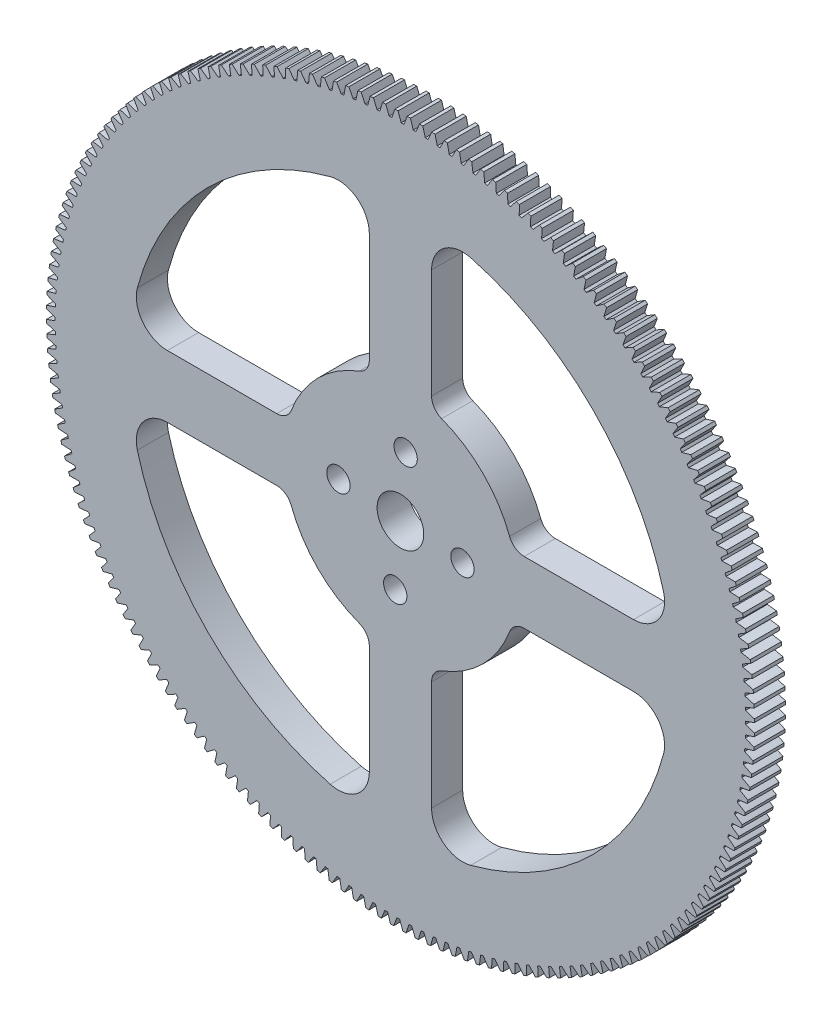
SolidWorks part; units mm, degrees
ref_plane "前视基准面" through (0, 0, 0) normal (0, 0, 1) x (1, 0, 0)
ref_plane "上视基准面" through (0, 0, 0) normal (0, 1, 0) x (1, 0, 0)
ref_plane "右视基准面" through (0, 0, 0) normal (1, 0, 0) x (0, 0, -1)
other "Configuration Table"
sketch "草图1" plane through (0, 0, 0) normal (0, 0, 1) x (1, 0, 0)
  line L0 (0.6614, 44.3701) -> (0.6707, 44.995) construction
  line L2 (1.8688, 45.4616) -> (1.8226, 44.3376) construction
  line L3 (1.0485, 44.3626) -> (1.0751, 45.4873) construction
  circle A1 centre (0, 0) radius 45
  circle A2 centre (0, 0) radius 44.375
  circle A3 centre (0, 0) radius 45.5
  spline S0 degree 4 poles (0, 42.2862) (0.0008, 42.3205) (0.0052, 42.4165) (0.023, 42.5977) (0.0651, 42.892) (0.1379, 43.2643) (0.254, 43.7417) (0.468, 44.4654) (0.7489, 45.2298) (1.0957, 46.0301) (1.4823, 46.8125) (1.813, 47.4272) (2.2381, 48.1599) (2.7851, 49.0228) (3.4712, 50.0031) (4.313, 51.085) (5.2227, 52.1448) (6.1787, 53.1621) (7.053, 54.0164) (7.8252, 54.7221) (8.4858, 55.2945) (9.0193, 55.7401) (9.7046, 56.2893) (10.3891, 56.8137) (11.1086, 57.3347) (11.9486, 57.9187) (12.7149, 58.4208) (13.388, 58.8471) (14.349, 59.42) (14.8483, 59.7051) (15.6315, 60.1402) (15.9948, 60.3271) (16.3146, 60.497) (16.4119, 60.5452) (16.4815, 60.5812) (16.519, 60.6007) knots 0 0 0 0 0 0.005377 0.015084 0.028532 0.04661 0.064855 0.092111 0.146842 0.174209 0.201575 0.228941 0.256307 0.307035 0.361767 0.4165 0.471232 0.525964 0.580697 0.608063 0.635429 0.662795 0.690161 0.744894 0.77226 0.799626 0.854358 0.881725 0.909091 0.954545 0.977273 0.988636 0.994318 1 1 1 1 1 construction
  spline S1 degree 4 poles (0.4494, 44.3727) (0.4658, 44.4223) (0.5607, 44.7057) (0.6639, 44.9863) (0.7741, 45.2642) (0.8695, 45.4917) knots 0.083923 0.083923 0.083923 0.083923 0.083923 0.092111 0.130798 0.130798 0.130798 0.130798 0.130798
  spline S2 degree 4 poles (1.6474, 44.3444) (1.6334, 44.3947) (1.552, 44.6823) (1.4622, 44.9675) (1.3652, 45.2502) (1.2807, 45.482) knots 0.083923 0.083923 0.083923 0.083923 0.083923 0.092111 0.130798 0.130798 0.130798 0.130798 0.130798
  spline S3 degree 4 poles (1.9978, 44.33) (2.0158, 44.379) (2.1206, 44.6589) (2.2335, 44.9358) (2.3533, 45.2096) (2.4566, 45.4336) knots 0.083923 0.083923 0.083923 0.083923 0.083923 0.092111 0.130798 0.130798 0.130798 0.130798 0.130798
  dimension "D1" = 90
  dimension "D2" = 91
  dimension "D3" = 88.75
  dimension "D5" = 0.5
  dimension "D6" = 1.5
sketch "草图2" plane through (0, 0, 0) normal (0, 0, 1) x (1, 0, 0)
  circle A0 centre (0, 0) radius 44.375 construction
  circle A1 centre (0, 0) radius 45.5 construction
  arc A2 (1.9978, 44.33) -> (1.6474, 44.3444) centre (0, 0) ccw
  arc A3 (1.2807, 45.482) -> (0.8695, 45.4917) centre (0, 0) ccw
  arc A4 (2.8672, 45.4096) -> (2.4566, 45.4336) centre (0, 0) ccw
  arc A5 (3.5436, 44.2333) -> (3.194, 44.2599) centre (0, 0) ccw
  arc A6 (4.4502, 45.2818) -> (4.0408, 45.3202) centre (0, 0) ccw
  arc A7 (5.0852, 44.0827) -> (4.7367, 44.1215) centre (0, 0) ccw
  arc A8 (6.0278, 45.099) -> (5.62, 45.1516) centre (0, 0) ccw
  arc A9 (6.6206, 43.8783) -> (6.2736, 43.9293) centre (0, 0) ccw
  arc A10 (7.5981, 44.8611) -> (7.1923, 44.928) centre (0, 0) ccw
  arc A11 (8.1479, 43.6206) -> (7.8029, 43.6836) centre (0, 0) ccw
  arc A12 (9.1591, 44.5686) -> (8.7559, 44.6496) centre (0, 0) ccw
  arc A13 (9.6652, 43.3096) -> (9.3227, 43.3846) centre (0, 0) ccw
  arc A14 (10.7089, 44.2218) -> (10.3088, 44.3168) centre (0, 0) ccw
  arc A15 (11.1708, 42.9459) -> (10.8311, 43.0329) centre (0, 0) ccw
  arc A16 (12.2457, 43.8211) -> (11.8491, 43.93) centre (0, 0) ccw
  arc A17 (12.6628, 42.5299) -> (12.3264, 42.6286) centre (0, 0) ccw
  arc A18 (13.7676, 43.3671) -> (13.3751, 43.4897) centre (0, 0) ccw
  arc A19 (14.1394, 42.0621) -> (13.8066, 42.1725) centre (0, 0) ccw
  arc A20 (15.2727, 42.8602) -> (14.8847, 42.9965) centre (0, 0) ccw
  arc A21 (15.5987, 41.543) -> (15.27, 41.665) centre (0, 0) ccw
  arc A22 (16.7592, 42.3011) -> (16.3762, 42.4508) centre (0, 0) ccw
  arc A23 (17.039, 40.9733) -> (16.7147, 41.1067) centre (0, 0) ccw
  arc A24 (18.2253, 41.6904) -> (17.8477, 41.8534) centre (0, 0) ccw
  arc A25 (18.4586, 40.3537) -> (18.1392, 40.4983) centre (0, 0) ccw
  arc A26 (19.6691, 41.029) -> (19.2975, 41.2051) centre (0, 0) ccw
  arc A27 (19.8557, 39.6849) -> (19.5415, 39.8406) centre (0, 0) ccw
  arc A28 (21.089, 40.3175) -> (20.7238, 40.5065) centre (0, 0) ccw
  arc A29 (21.2286, 38.9678) -> (20.92, 39.1343) centre (0, 0) ccw
  arc A30 (22.4832, 39.557) -> (22.1248, 39.7586) centre (0, 0) ccw
  arc A31 (22.5756, 38.2032) -> (22.273, 38.3804) centre (0, 0) ccw
  arc A32 (23.8501, 38.7482) -> (23.4989, 38.9622) centre (0, 0) ccw
  arc A33 (23.8951, 37.392) -> (23.5989, 37.5797) centre (0, 0) ccw
  arc A34 (25.1878, 37.8923) -> (24.8443, 38.1184) centre (0, 0) ccw
  arc A35 (25.1855, 36.5353) -> (24.896, 36.7332) centre (0, 0) ccw
  arc A36 (26.4949, 36.9901) -> (26.1595, 37.2281) centre (0, 0) ccw
  arc A37 (26.4452, 35.6341) -> (26.1628, 35.842) centre (0, 0) ccw
  arc A38 (27.7697, 36.0429) -> (27.4428, 36.2924) centre (0, 0) ccw
  arc A39 (27.6727, 34.6895) -> (27.3978, 34.9071) centre (0, 0) ccw
  arc A40 (29.0107, 35.0518) -> (28.6927, 35.3126) centre (0, 0) ccw
  arc A41 (28.8665, 33.7026) -> (28.5993, 33.9296) centre (0, 0) ccw
  arc A42 (30.2163, 34.018) -> (29.9076, 34.2897) centre (0, 0) ccw
  arc A43 (30.0252, 32.6746) -> (29.766, 32.9109) centre (0, 0) ccw
  arc A44 (31.3851, 32.9428) -> (31.0861, 33.2251) centre (0, 0) ccw
  arc A45 (31.1472, 31.6069) -> (30.8965, 31.852) centre (0, 0) ccw
  arc A46 (32.5157, 31.8274) -> (32.2267, 32.12) centre (0, 0) ccw
  arc A47 (32.2313, 30.5006) -> (31.9893, 30.7543) centre (0, 0) ccw
  arc A48 (33.6066, 30.6732) -> (33.328, 30.9757) centre (0, 0) ccw
  arc A49 (33.2761, 29.3571) -> (33.0431, 29.6192) centre (0, 0) ccw
  arc A50 (34.6566, 29.4817) -> (34.3887, 29.7937) centre (0, 0) ccw
  arc A51 (34.2804, 28.1779) -> (34.0567, 28.4479) centre (0, 0) ccw
  arc A52 (35.6644, 28.2542) -> (35.4076, 28.5754) centre (0, 0) ccw
  arc A53 (35.2429, 26.9644) -> (35.0287, 27.242) centre (0, 0) ccw
  arc A54 (36.6287, 26.9923) -> (36.3833, 27.3223) centre (0, 0) ccw
  arc A55 (36.1625, 25.718) -> (35.9581, 26.003) centre (0, 0) ccw
  arc A56 (37.5484, 25.6976) -> (37.3147, 26.0359) centre (0, 0) ccw
  arc A57 (37.038, 24.4403) -> (36.8437, 24.7322) centre (0, 0) ccw
  arc A58 (38.4224, 24.3715) -> (38.2006, 24.7178) centre (0, 0) ccw
  arc A59 (37.8684, 23.1328) -> (37.6844, 23.4313) centre (0, 0) ccw
  arc A60 (39.2495, 23.0157) -> (39.0399, 23.3695) centre (0, 0) ccw
  arc A61 (38.6526, 21.7971) -> (38.4792, 22.1019) centre (0, 0) ccw
  arc A62 (40.0289, 21.6319) -> (39.8317, 21.9928) centre (0, 0) ccw
  arc A63 (39.3898, 20.4349) -> (39.2271, 20.7455) centre (0, 0) ccw
  arc A64 (40.7594, 20.2217) -> (40.575, 20.5893) centre (0, 0) ccw
  arc A65 (40.079, 19.0478) -> (39.9272, 19.3639) centre (0, 0) ccw
  arc A66 (41.4403, 18.7869) -> (41.2688, 19.1607) centre (0, 0) ccw
  arc A67 (40.7193, 17.6374) -> (40.5787, 17.9586) centre (0, 0) ccw
  arc A68 (42.0707, 17.3292) -> (41.9124, 17.7088) centre (0, 0) ccw
  arc A69 (41.31, 16.2056) -> (41.1807, 16.5315) centre (0, 0) ccw
  arc A70 (42.6499, 15.8504) -> (42.5049, 16.2353) centre (0, 0) ccw
  arc A71 (41.8504, 14.754) -> (41.7326, 15.0843) centre (0, 0) ccw
  arc A72 (43.1771, 14.3523) -> (43.0456, 14.742) centre (0, 0) ccw
  arc A73 (42.3399, 13.2845) -> (42.2336, 13.6186) centre (0, 0) ccw
  arc A74 (43.6517, 12.8367) -> (43.5339, 13.2307) centre (0, 0) ccw
  arc A75 (42.7777, 11.7987) -> (42.6831, 12.1364) centre (0, 0) ccw
  arc A76 (44.0731, 11.3055) -> (43.9691, 11.7034) centre (0, 0) ccw
  arc A77 (43.1634, 10.2986) -> (43.0807, 10.6394) centre (0, 0) ccw
  arc A78 (44.4408, 9.7605) -> (44.3508, 10.1617) centre (0, 0) ccw
  arc A79 (43.4965, 8.786) -> (43.4257, 9.1294) centre (0, 0) ccw
  arc A80 (44.7543, 8.2036) -> (44.6784, 8.6077) centre (0, 0) ccw
  arc A81 (43.7766, 7.2626) -> (43.7179, 7.6083) centre (0, 0) ccw
  arc A82 (45.0134, 6.6367) -> (44.9516, 7.0432) centre (0, 0) ccw
  arc A83 (44.0034, 5.7304) -> (43.9568, 6.0779) centre (0, 0) ccw
  arc A84 (45.2176, 5.0617) -> (45.17, 5.4701) centre (0, 0) ccw
  arc A85 (44.1766, 4.1912) -> (44.1421, 4.5402) centre (0, 0) ccw
  arc A86 (45.3667, 3.4805) -> (45.3334, 3.8904) centre (0, 0) ccw
  arc A87 (44.296, 2.6469) -> (44.2737, 2.9969) centre (0, 0) ccw
  arc A88 (45.4605, 1.8951) -> (45.4415, 2.3059) centre (0, 0) ccw
  arc A89 (44.3614, 1.0994) -> (44.3513, 1.4499) centre (0, 0) ccw
  arc A90 (45.499, 0.3074) -> (45.4943, 0.7186) centre (0, 0) ccw
  arc A91 (44.3727, -0.4494) -> (44.3749, -0.0988) centre (0, 0) ccw
  arc A92 (45.482, -1.2807) -> (45.4917, -0.8695) centre (0, 0) ccw
  arc A93 (44.33, -1.9978) -> (44.3444, -1.6474) centre (0, 0) ccw
  arc A94 (45.4096, -2.8672) -> (45.4336, -2.4566) centre (0, 0) ccw
  arc A95 (44.2333, -3.5436) -> (44.2599, -3.194) centre (0, 0) ccw
  arc A96 (45.2818, -4.4502) -> (45.3202, -4.0408) centre (0, 0) ccw
  arc A97 (44.0827, -5.0852) -> (44.1215, -4.7367) centre (0, 0) ccw
  arc A98 (45.099, -6.0278) -> (45.1516, -5.62) centre (0, 0) ccw
  arc A99 (43.8783, -6.6206) -> (43.9293, -6.2736) centre (0, 0) ccw
  arc A100 (44.8611, -7.5981) -> (44.928, -7.1923) centre (0, 0) ccw
  arc A101 (43.6206, -8.1479) -> (43.6836, -7.8029) centre (0, 0) ccw
  arc A102 (44.5686, -9.1591) -> (44.6496, -8.7559) centre (0, 0) ccw
  arc A103 (43.3096, -9.6652) -> (43.3846, -9.3227) centre (0, 0) ccw
  arc A104 (44.2218, -10.7089) -> (44.3168, -10.3088) centre (0, 0) ccw
  arc A105 (42.9459, -11.1708) -> (43.0329, -10.8311) centre (0, 0) ccw
  arc A106 (43.8211, -12.2457) -> (43.93, -11.8491) centre (0, 0) ccw
  arc A107 (42.5299, -12.6628) -> (42.6286, -12.3264) centre (0, 0) ccw
  arc A108 (43.3671, -13.7676) -> (43.4897, -13.3751) centre (0, 0) ccw
  arc A109 (42.0621, -14.1394) -> (42.1725, -13.8066) centre (0, 0) ccw
  arc A110 (42.8602, -15.2727) -> (42.9965, -14.8847) centre (0, 0) ccw
  arc A111 (41.543, -15.5987) -> (41.665, -15.27) centre (0, 0) ccw
  arc A112 (42.3011, -16.7592) -> (42.4508, -16.3762) centre (0, 0) ccw
  arc A113 (40.9733, -17.039) -> (41.1067, -16.7147) centre (0, 0) ccw
  arc A114 (41.6904, -18.2253) -> (41.8534, -17.8477) centre (0, 0) ccw
  arc A115 (40.3537, -18.4586) -> (40.4983, -18.1392) centre (0, 0) ccw
  arc A116 (41.029, -19.6691) -> (41.2051, -19.2975) centre (0, 0) ccw
  arc A117 (39.6849, -19.8557) -> (39.8406, -19.5415) centre (0, 0) ccw
  arc A118 (40.3175, -21.089) -> (40.5065, -20.7238) centre (0, 0) ccw
  arc A119 (38.9678, -21.2286) -> (39.1343, -20.92) centre (0, 0) ccw
  arc A120 (39.557, -22.4832) -> (39.7586, -22.1248) centre (0, 0) ccw
  arc A121 (38.2032, -22.5756) -> (38.3804, -22.273) centre (0, 0) ccw
  arc A122 (38.7482, -23.8501) -> (38.9622, -23.4989) centre (0, 0) ccw
  arc A123 (37.392, -23.8951) -> (37.5797, -23.5989) centre (0, 0) ccw
  arc A124 (37.8923, -25.1878) -> (38.1184, -24.8443) centre (0, 0) ccw
  arc A125 (36.5353, -25.1855) -> (36.7332, -24.896) centre (0, 0) ccw
  arc A126 (36.9901, -26.4949) -> (37.2281, -26.1595) centre (0, 0) ccw
  arc A127 (35.6341, -26.4452) -> (35.842, -26.1628) centre (0, 0) ccw
  arc A128 (36.0429, -27.7697) -> (36.2924, -27.4428) centre (0, 0) ccw
  arc A129 (34.6895, -27.6727) -> (34.9071, -27.3978) centre (0, 0) ccw
  arc A130 (35.0518, -29.0107) -> (35.3126, -28.6927) centre (0, 0) ccw
  arc A131 (33.7026, -28.8665) -> (33.9296, -28.5993) centre (0, 0) ccw
  arc A132 (34.018, -30.2163) -> (34.2897, -29.9076) centre (0, 0) ccw
  arc A133 (32.6746, -30.0252) -> (32.9109, -29.766) centre (0, 0) ccw
  arc A134 (32.9428, -31.3851) -> (33.2251, -31.0861) centre (0, 0) ccw
  arc A135 (31.6069, -31.1472) -> (31.852, -30.8965) centre (0, 0) ccw
  arc A136 (31.8274, -32.5157) -> (32.12, -32.2267) centre (0, 0) ccw
  arc A137 (30.5006, -32.2313) -> (30.7543, -31.9893) centre (0, 0) ccw
  arc A138 (30.6732, -33.6066) -> (30.9757, -33.328) centre (0, 0) ccw
  arc A139 (29.3571, -33.2761) -> (29.6192, -33.0431) centre (0, 0) ccw
  arc A140 (29.4817, -34.6566) -> (29.7937, -34.3887) centre (0, 0) ccw
  arc A141 (28.1779, -34.2804) -> (28.4479, -34.0567) centre (0, 0) ccw
  arc A142 (28.2542, -35.6644) -> (28.5754, -35.4076) centre (0, 0) ccw
  arc A143 (26.9644, -35.2429) -> (27.242, -35.0287) centre (0, 0) ccw
  arc A144 (26.9923, -36.6287) -> (27.3223, -36.3833) centre (0, 0) ccw
  arc A145 (25.718, -36.1625) -> (26.003, -35.9581) centre (0, 0) ccw
  arc A146 (25.6976, -37.5484) -> (26.0359, -37.3147) centre (0, 0) ccw
  arc A147 (24.4403, -37.038) -> (24.7322, -36.8437) centre (0, 0) ccw
  arc A148 (24.3715, -38.4224) -> (24.7178, -38.2006) centre (0, 0) ccw
  arc A149 (23.1328, -37.8684) -> (23.4313, -37.6844) centre (0, 0) ccw
  arc A150 (23.0157, -39.2495) -> (23.3695, -39.0399) centre (0, 0) ccw
  arc A151 (21.7971, -38.6526) -> (22.1019, -38.4792) centre (0, 0) ccw
  arc A152 (21.6319, -40.0289) -> (21.9928, -39.8317) centre (0, 0) ccw
  arc A153 (20.4349, -39.3898) -> (20.7455, -39.2271) centre (0, 0) ccw
  arc A154 (20.2217, -40.7594) -> (20.5893, -40.575) centre (0, 0) ccw
  arc A155 (19.0478, -40.079) -> (19.3639, -39.9272) centre (0, 0) ccw
  arc A156 (18.7869, -41.4403) -> (19.1607, -41.2688) centre (0, 0) ccw
  arc A157 (17.6374, -40.7193) -> (17.9586, -40.5787) centre (0, 0) ccw
  arc A158 (17.3292, -42.0707) -> (17.7088, -41.9124) centre (0, 0) ccw
  arc A159 (16.2056, -41.31) -> (16.5315, -41.1807) centre (0, 0) ccw
  arc A160 (15.8504, -42.6499) -> (16.2353, -42.5049) centre (0, 0) ccw
  arc A161 (14.754, -41.8504) -> (15.0843, -41.7326) centre (0, 0) ccw
  arc A162 (14.3523, -43.1771) -> (14.742, -43.0456) centre (0, 0) ccw
  arc A163 (13.2845, -42.3399) -> (13.6186, -42.2336) centre (0, 0) ccw
  arc A164 (12.8367, -43.6517) -> (13.2307, -43.5339) centre (0, 0) ccw
  arc A165 (11.7987, -42.7777) -> (12.1364, -42.6831) centre (0, 0) ccw
  arc A166 (11.3055, -44.0731) -> (11.7034, -43.9691) centre (0, 0) ccw
  arc A167 (10.2986, -43.1634) -> (10.6394, -43.0807) centre (0, 0) ccw
  arc A168 (9.7605, -44.4408) -> (10.1617, -44.3508) centre (0, 0) ccw
  arc A169 (8.786, -43.4965) -> (9.1294, -43.4257) centre (0, 0) ccw
  arc A170 (8.2036, -44.7543) -> (8.6077, -44.6784) centre (0, 0) ccw
  arc A171 (7.2626, -43.7766) -> (7.6083, -43.7179) centre (0, 0) ccw
  arc A172 (6.6367, -45.0134) -> (7.0432, -44.9516) centre (0, 0) ccw
  arc A173 (5.7304, -44.0034) -> (6.0779, -43.9568) centre (0, 0) ccw
  arc A174 (5.0617, -45.2176) -> (5.4701, -45.17) centre (0, 0) ccw
  arc A175 (4.1912, -44.1766) -> (4.5402, -44.1421) centre (0, 0) ccw
  arc A176 (3.4805, -45.3667) -> (3.8904, -45.3334) centre (0, 0) ccw
  arc A177 (2.6469, -44.296) -> (2.9969, -44.2737) centre (0, 0) ccw
  arc A178 (1.8951, -45.4605) -> (2.3059, -45.4415) centre (0, 0) ccw
  arc A179 (1.0994, -44.3614) -> (1.4499, -44.3513) centre (0, 0) ccw
  arc A180 (0.3074, -45.499) -> (0.7186, -45.4943) centre (0, 0) ccw
  arc A181 (-0.4494, -44.3727) -> (-0.0988, -44.3749) centre (0, 0) ccw
  arc A182 (-1.2807, -45.482) -> (-0.8695, -45.4917) centre (0, 0) ccw
  arc A183 (-1.9978, -44.33) -> (-1.6474, -44.3444) centre (0, 0) ccw
  arc A184 (-2.8672, -45.4096) -> (-2.4566, -45.4336) centre (0, 0) ccw
  arc A185 (-3.5436, -44.2333) -> (-3.194, -44.2599) centre (0, 0) ccw
  arc A186 (-4.4502, -45.2818) -> (-4.0408, -45.3202) centre (0, 0) ccw
  arc A187 (-5.0852, -44.0827) -> (-4.7367, -44.1215) centre (0, 0) ccw
  arc A188 (-6.0278, -45.099) -> (-5.62, -45.1516) centre (0, 0) ccw
  arc A189 (-6.6206, -43.8783) -> (-6.2736, -43.9293) centre (0, 0) ccw
  arc A190 (-7.5981, -44.8611) -> (-7.1923, -44.928) centre (0, 0) ccw
  arc A191 (-8.1479, -43.6206) -> (-7.8029, -43.6836) centre (0, 0) ccw
  arc A192 (-9.1591, -44.5686) -> (-8.7559, -44.6496) centre (0, 0) ccw
  arc A193 (-9.6652, -43.3096) -> (-9.3227, -43.3846) centre (0, 0) ccw
  arc A194 (-10.7089, -44.2218) -> (-10.3088, -44.3168) centre (0, 0) ccw
  arc A195 (-11.1708, -42.9459) -> (-10.8311, -43.0329) centre (0, 0) ccw
  arc A196 (-12.2457, -43.8211) -> (-11.8491, -43.93) centre (0, 0) ccw
  arc A197 (-12.6628, -42.5299) -> (-12.3264, -42.6286) centre (0, 0) ccw
  arc A198 (-13.7676, -43.3671) -> (-13.3751, -43.4897) centre (0, 0) ccw
  arc A199 (-14.1394, -42.0621) -> (-13.8066, -42.1725) centre (0, 0) ccw
  arc A200 (-15.2727, -42.8602) -> (-14.8847, -42.9965) centre (0, 0) ccw
  arc A201 (-15.5987, -41.543) -> (-15.27, -41.665) centre (0, 0) ccw
  arc A202 (-16.7592, -42.3011) -> (-16.3762, -42.4508) centre (0, 0) ccw
  arc A203 (-17.039, -40.9733) -> (-16.7147, -41.1067) centre (0, 0) ccw
  arc A204 (-18.2253, -41.6904) -> (-17.8477, -41.8534) centre (0, 0) ccw
  arc A205 (-18.4586, -40.3537) -> (-18.1392, -40.4983) centre (0, 0) ccw
  arc A206 (-19.6691, -41.029) -> (-19.2975, -41.2051) centre (0, 0) ccw
  arc A207 (-19.8557, -39.6849) -> (-19.5415, -39.8406) centre (0, 0) ccw
  arc A208 (-21.089, -40.3175) -> (-20.7238, -40.5065) centre (0, 0) ccw
  arc A209 (-21.2286, -38.9678) -> (-20.92, -39.1343) centre (0, 0) ccw
  arc A210 (-22.4832, -39.557) -> (-22.1248, -39.7586) centre (0, 0) ccw
  arc A211 (-22.5756, -38.2032) -> (-22.273, -38.3804) centre (0, 0) ccw
  arc A212 (-23.8501, -38.7482) -> (-23.4989, -38.9622) centre (0, 0) ccw
  arc A213 (-23.8951, -37.392) -> (-23.5989, -37.5797) centre (0, 0) ccw
  arc A214 (-25.1878, -37.8923) -> (-24.8443, -38.1184) centre (0, 0) ccw
  arc A215 (-25.1855, -36.5353) -> (-24.896, -36.7332) centre (0, 0) ccw
  arc A216 (-26.4949, -36.9901) -> (-26.1595, -37.2281) centre (0, 0) ccw
  arc A217 (-26.4452, -35.6341) -> (-26.1628, -35.842) centre (0, 0) ccw
  arc A218 (-27.7697, -36.0429) -> (-27.4428, -36.2924) centre (0, 0) ccw
  arc A219 (-27.6727, -34.6895) -> (-27.3978, -34.9071) centre (0, 0) ccw
  arc A220 (-29.0107, -35.0518) -> (-28.6927, -35.3126) centre (0, 0) ccw
  arc A221 (-28.8665, -33.7026) -> (-28.5993, -33.9296) centre (0, 0) ccw
  arc A222 (-30.2163, -34.018) -> (-29.9076, -34.2897) centre (0, 0) ccw
  arc A223 (-30.0252, -32.6746) -> (-29.766, -32.9109) centre (0, 0) ccw
  arc A224 (-31.3851, -32.9428) -> (-31.0861, -33.2251) centre (0, 0) ccw
  arc A225 (-31.1472, -31.6069) -> (-30.8965, -31.852) centre (0, 0) ccw
  arc A226 (-32.5157, -31.8274) -> (-32.2267, -32.12) centre (0, 0) ccw
  arc A227 (-32.2313, -30.5006) -> (-31.9893, -30.7543) centre (0, 0) ccw
  arc A228 (-33.6066, -30.6732) -> (-33.328, -30.9757) centre (0, 0) ccw
  arc A229 (-33.2761, -29.3571) -> (-33.0431, -29.6192) centre (0, 0) ccw
  arc A230 (-34.6566, -29.4817) -> (-34.3887, -29.7937) centre (0, 0) ccw
  arc A231 (-34.2804, -28.1779) -> (-34.0567, -28.4479) centre (0, 0) ccw
  arc A232 (-35.6644, -28.2542) -> (-35.4076, -28.5754) centre (0, 0) ccw
  arc A233 (-35.2429, -26.9644) -> (-35.0287, -27.242) centre (0, 0) ccw
  arc A234 (-36.6287, -26.9923) -> (-36.3833, -27.3223) centre (0, 0) ccw
  arc A235 (-36.1625, -25.718) -> (-35.9581, -26.003) centre (0, 0) ccw
  arc A236 (-37.5484, -25.6976) -> (-37.3147, -26.0359) centre (0, 0) ccw
  arc A237 (-37.038, -24.4403) -> (-36.8437, -24.7322) centre (0, 0) ccw
  arc A238 (-38.4224, -24.3715) -> (-38.2006, -24.7178) centre (0, 0) ccw
  arc A239 (-37.8684, -23.1328) -> (-37.6844, -23.4313) centre (0, 0) ccw
  arc A240 (-39.2495, -23.0157) -> (-39.0399, -23.3695) centre (0, 0) ccw
  arc A241 (-38.6526, -21.7971) -> (-38.4792, -22.1019) centre (0, 0) ccw
  arc A242 (-40.0289, -21.6319) -> (-39.8317, -21.9928) centre (0, 0) ccw
  arc A243 (-39.3898, -20.4349) -> (-39.2271, -20.7455) centre (0, 0) ccw
  arc A244 (-40.7594, -20.2217) -> (-40.575, -20.5893) centre (0, 0) ccw
  arc A245 (-40.079, -19.0478) -> (-39.9272, -19.3639) centre (0, 0) ccw
  arc A246 (-41.4403, -18.7869) -> (-41.2688, -19.1607) centre (0, 0) ccw
  arc A247 (-40.7193, -17.6374) -> (-40.5787, -17.9586) centre (0, 0) ccw
  arc A248 (-42.0707, -17.3292) -> (-41.9124, -17.7088) centre (0, 0) ccw
  arc A249 (-41.31, -16.2056) -> (-41.1807, -16.5315) centre (0, 0) ccw
  arc A250 (-42.6499, -15.8504) -> (-42.5049, -16.2353) centre (0, 0) ccw
  arc A251 (-41.8504, -14.754) -> (-41.7326, -15.0843) centre (0, 0) ccw
  arc A252 (-43.1771, -14.3523) -> (-43.0456, -14.742) centre (0, 0) ccw
  arc A253 (-42.3399, -13.2845) -> (-42.2336, -13.6186) centre (0, 0) ccw
  arc A254 (-43.6517, -12.8367) -> (-43.5339, -13.2307) centre (0, 0) ccw
  arc A255 (-42.7777, -11.7987) -> (-42.6831, -12.1364) centre (0, 0) ccw
  arc A256 (-44.0731, -11.3055) -> (-43.9691, -11.7034) centre (0, 0) ccw
  arc A257 (-43.1634, -10.2986) -> (-43.0807, -10.6394) centre (0, 0) ccw
  arc A258 (-44.4408, -9.7605) -> (-44.3508, -10.1617) centre (0, 0) ccw
  arc A259 (-43.4965, -8.786) -> (-43.4257, -9.1294) centre (0, 0) ccw
  arc A260 (-44.7543, -8.2036) -> (-44.6784, -8.6077) centre (0, 0) ccw
  arc A261 (-43.7766, -7.2626) -> (-43.7179, -7.6083) centre (0, 0) ccw
  arc A262 (-45.0134, -6.6367) -> (-44.9516, -7.0432) centre (0, 0) ccw
  arc A263 (-44.0034, -5.7304) -> (-43.9568, -6.0779) centre (0, 0) ccw
  arc A264 (-45.2176, -5.0617) -> (-45.17, -5.4701) centre (0, 0) ccw
  arc A265 (-44.1766, -4.1912) -> (-44.1421, -4.5402) centre (0, 0) ccw
  arc A266 (-45.3667, -3.4805) -> (-45.3334, -3.8904) centre (0, 0) ccw
  arc A267 (-44.296, -2.6469) -> (-44.2737, -2.9969) centre (0, 0) ccw
  arc A268 (-45.4605, -1.8951) -> (-45.4415, -2.3059) centre (0, 0) ccw
  arc A269 (-44.3614, -1.0994) -> (-44.3513, -1.4499) centre (0, 0) ccw
  arc A270 (-45.499, -0.3074) -> (-45.4943, -0.7186) centre (0, 0) ccw
  arc A271 (-44.3727, 0.4494) -> (-44.3749, 0.0988) centre (0, 0) ccw
  arc A272 (-45.482, 1.2807) -> (-45.4917, 0.8695) centre (0, 0) ccw
  arc A273 (-44.33, 1.9978) -> (-44.3444, 1.6474) centre (0, 0) ccw
  arc A274 (-45.4096, 2.8672) -> (-45.4336, 2.4566) centre (0, 0) ccw
  arc A275 (-44.2333, 3.5436) -> (-44.2599, 3.194) centre (0, 0) ccw
  arc A276 (-45.2818, 4.4502) -> (-45.3202, 4.0408) centre (0, 0) ccw
  arc A277 (-44.0827, 5.0852) -> (-44.1215, 4.7367) centre (0, 0) ccw
  arc A278 (-45.099, 6.0278) -> (-45.1516, 5.62) centre (0, 0) ccw
  arc A279 (-43.8783, 6.6206) -> (-43.9293, 6.2736) centre (0, 0) ccw
  arc A280 (-44.8611, 7.5981) -> (-44.928, 7.1923) centre (0, 0) ccw
  arc A281 (-43.6206, 8.1479) -> (-43.6836, 7.8029) centre (0, 0) ccw
  arc A282 (-44.5686, 9.1591) -> (-44.6496, 8.7559) centre (0, 0) ccw
  arc A283 (-43.3096, 9.6652) -> (-43.3846, 9.3227) centre (0, 0) ccw
  arc A284 (-44.2218, 10.7089) -> (-44.3168, 10.3088) centre (0, 0) ccw
  arc A285 (-42.9459, 11.1708) -> (-43.0329, 10.8311) centre (0, 0) ccw
  arc A286 (-43.8211, 12.2457) -> (-43.93, 11.8491) centre (0, 0) ccw
  arc A287 (-42.5299, 12.6628) -> (-42.6286, 12.3264) centre (0, 0) ccw
  arc A288 (-43.3671, 13.7676) -> (-43.4897, 13.3751) centre (0, 0) ccw
  arc A289 (-42.0621, 14.1394) -> (-42.1725, 13.8066) centre (0, 0) ccw
  arc A290 (-42.8602, 15.2727) -> (-42.9965, 14.8847) centre (0, 0) ccw
  arc A291 (-41.543, 15.5987) -> (-41.665, 15.27) centre (0, 0) ccw
  arc A292 (-42.3011, 16.7592) -> (-42.4508, 16.3762) centre (0, 0) ccw
  arc A293 (-40.9733, 17.039) -> (-41.1067, 16.7147) centre (0, 0) ccw
  arc A294 (-41.6904, 18.2253) -> (-41.8534, 17.8477) centre (0, 0) ccw
  arc A295 (-40.3537, 18.4586) -> (-40.4983, 18.1392) centre (0, 0) ccw
  arc A296 (-41.029, 19.6691) -> (-41.2051, 19.2975) centre (0, 0) ccw
  arc A297 (-39.6849, 19.8557) -> (-39.8406, 19.5415) centre (0, 0) ccw
  arc A298 (-40.3175, 21.089) -> (-40.5065, 20.7238) centre (0, 0) ccw
  arc A299 (-38.9678, 21.2286) -> (-39.1343, 20.92) centre (0, 0) ccw
  arc A300 (-39.557, 22.4832) -> (-39.7586, 22.1248) centre (0, 0) ccw
  arc A301 (-38.2032, 22.5756) -> (-38.3804, 22.273) centre (0, 0) ccw
  arc A302 (-38.7482, 23.8501) -> (-38.9622, 23.4989) centre (0, 0) ccw
  arc A303 (-37.392, 23.8951) -> (-37.5797, 23.5989) centre (0, 0) ccw
  arc A304 (-37.8923, 25.1878) -> (-38.1184, 24.8443) centre (0, 0) ccw
  arc A305 (-36.5353, 25.1855) -> (-36.7332, 24.896) centre (0, 0) ccw
  arc A306 (-36.9901, 26.4949) -> (-37.2281, 26.1595) centre (0, 0) ccw
  arc A307 (-35.6341, 26.4452) -> (-35.842, 26.1628) centre (0, 0) ccw
  arc A308 (-36.0429, 27.7697) -> (-36.2924, 27.4428) centre (0, 0) ccw
  arc A309 (-34.6895, 27.6727) -> (-34.9071, 27.3978) centre (0, 0) ccw
  arc A310 (-35.0518, 29.0107) -> (-35.3126, 28.6927) centre (0, 0) ccw
  arc A311 (-33.7026, 28.8665) -> (-33.9296, 28.5993) centre (0, 0) ccw
  arc A312 (-34.018, 30.2163) -> (-34.2897, 29.9076) centre (0, 0) ccw
  arc A313 (-32.6746, 30.0252) -> (-32.9109, 29.766) centre (0, 0) ccw
  arc A314 (-32.9428, 31.3851) -> (-33.2251, 31.0861) centre (0, 0) ccw
  arc A315 (-31.6069, 31.1472) -> (-31.852, 30.8965) centre (0, 0) ccw
  arc A316 (-31.8274, 32.5157) -> (-32.12, 32.2267) centre (0, 0) ccw
  arc A317 (-30.5006, 32.2313) -> (-30.7543, 31.9893) centre (0, 0) ccw
  arc A318 (-30.6732, 33.6066) -> (-30.9757, 33.328) centre (0, 0) ccw
  arc A319 (-29.3571, 33.2761) -> (-29.6192, 33.0431) centre (0, 0) ccw
  arc A320 (-29.4817, 34.6566) -> (-29.7937, 34.3887) centre (0, 0) ccw
  arc A321 (-28.1779, 34.2804) -> (-28.4479, 34.0567) centre (0, 0) ccw
  arc A322 (-28.2542, 35.6644) -> (-28.5754, 35.4076) centre (0, 0) ccw
  arc A323 (-26.9644, 35.2429) -> (-27.242, 35.0287) centre (0, 0) ccw
  arc A324 (-26.9923, 36.6287) -> (-27.3223, 36.3833) centre (0, 0) ccw
  arc A325 (-25.718, 36.1625) -> (-26.003, 35.9581) centre (0, 0) ccw
  arc A326 (-25.6976, 37.5484) -> (-26.0359, 37.3147) centre (0, 0) ccw
  arc A327 (-24.4403, 37.038) -> (-24.7322, 36.8437) centre (0, 0) ccw
  arc A328 (-24.3715, 38.4224) -> (-24.7178, 38.2006) centre (0, 0) ccw
  arc A329 (-23.1328, 37.8684) -> (-23.4313, 37.6844) centre (0, 0) ccw
  arc A330 (-23.0157, 39.2495) -> (-23.3695, 39.0399) centre (0, 0) ccw
  arc A331 (-21.7971, 38.6526) -> (-22.1019, 38.4792) centre (0, 0) ccw
  arc A332 (-21.6319, 40.0289) -> (-21.9928, 39.8317) centre (0, 0) ccw
  arc A333 (-20.4349, 39.3898) -> (-20.7455, 39.2271) centre (0, 0) ccw
  arc A334 (-20.2217, 40.7594) -> (-20.5893, 40.575) centre (0, 0) ccw
  arc A335 (-19.0478, 40.079) -> (-19.3639, 39.9272) centre (0, 0) ccw
  arc A336 (-18.7869, 41.4403) -> (-19.1607, 41.2688) centre (0, 0) ccw
  arc A337 (-17.6374, 40.7193) -> (-17.9586, 40.5787) centre (0, 0) ccw
  arc A338 (-17.3292, 42.0707) -> (-17.7088, 41.9124) centre (0, 0) ccw
  arc A339 (-16.2056, 41.31) -> (-16.5315, 41.1807) centre (0, 0) ccw
  arc A340 (-15.8504, 42.6499) -> (-16.2353, 42.5049) centre (0, 0) ccw
  arc A341 (-14.754, 41.8504) -> (-15.0843, 41.7326) centre (0, 0) ccw
  arc A342 (-14.3523, 43.1771) -> (-14.742, 43.0456) centre (0, 0) ccw
  arc A343 (-13.2845, 42.3399) -> (-13.6186, 42.2336) centre (0, 0) ccw
  arc A344 (-12.8367, 43.6517) -> (-13.2307, 43.5339) centre (0, 0) ccw
  arc A345 (-11.7987, 42.7777) -> (-12.1364, 42.6831) centre (0, 0) ccw
  arc A346 (-11.3055, 44.0731) -> (-11.7034, 43.9691) centre (0, 0) ccw
  arc A347 (-10.2986, 43.1634) -> (-10.6394, 43.0807) centre (0, 0) ccw
  arc A348 (-9.7605, 44.4408) -> (-10.1617, 44.3508) centre (0, 0) ccw
  arc A349 (-8.786, 43.4965) -> (-9.1294, 43.4257) centre (0, 0) ccw
  arc A350 (-8.2036, 44.7543) -> (-8.6077, 44.6784) centre (0, 0) ccw
  arc A351 (-7.2626, 43.7766) -> (-7.6083, 43.7179) centre (0, 0) ccw
  arc A352 (-6.6367, 45.0134) -> (-7.0432, 44.9516) centre (0, 0) ccw
  arc A353 (-5.7304, 44.0034) -> (-6.0779, 43.9568) centre (0, 0) ccw
  arc A354 (-5.0617, 45.2176) -> (-5.4701, 45.17) centre (0, 0) ccw
  arc A355 (-4.1912, 44.1766) -> (-4.5402, 44.1421) centre (0, 0) ccw
  arc A356 (-3.4805, 45.3667) -> (-3.8904, 45.3334) centre (0, 0) ccw
  arc A357 (-2.6469, 44.296) -> (-2.9969, 44.2737) centre (0, 0) ccw
  arc A358 (-1.8951, 45.4605) -> (-2.3059, 45.4415) centre (0, 0) ccw
  arc A359 (-1.0994, 44.3614) -> (-1.4499, 44.3513) centre (0, 0) ccw
  arc A360 (-0.3074, 45.499) -> (-0.7186, 45.4943) centre (0, 0) ccw
  arc A361 (0.4494, 44.3727) -> (0.0988, 44.3749) centre (0, 0) ccw
  spline S1 degree 4 poles (-1997.6629, 82.7606) (-53.3576, 9.8462) (75.0138, 42.7847) (-78.3244, 67.8463) (52.0245, 65.2516) (-1994.8648, 167.3698) knots -1.448251 -1.448251 -1.448251 -1.448251 -1.448251 0.092111 2.372802 2.372802 2.372802 2.372802 2.372802 only from (1.6474, 44.3444) to (1.2807, 45.482) construction
  spline S2 degree 4 poles (1999.3267, -11.7059) (53.935, 7.2803) (-72.8906, 46.2084) (81.1309, 64.0161) (-48.4685, 67.6167) (2000.444, 73.3197) knots -1.449392 -1.449392 -1.449392 -1.449392 -1.449392 0.092111 2.36688 2.36688 2.36688 2.36688 2.36688 only from (0.4494, 44.3727) to (0.8695, 45.4917) construction
  spline S3 degree 4 poles (1.9978, 44.33) (2.0158, 44.379) (2.1206, 44.6589) (2.2335, 44.9358) (2.3533, 45.2096) (2.4566, 45.4336) knots 0.083923 0.083923 0.083923 0.083923 0.083923 0.092111 0.130798 0.130798 0.130798 0.130798 0.130798
  spline S4 degree 4 poles (1.6474, 44.3444) (1.6334, 44.3947) (1.552, 44.6823) (1.4622, 44.9675) (1.3652, 45.2502) (1.2807, 45.482) knots 0.083923 0.083923 0.083923 0.083923 0.083923 0.092111 0.130798 0.130798 0.130798 0.130798 0.130798
  spline S5 degree 4 poles (0.4494, 44.3727) (0.4658, 44.4223) (0.5607, 44.7057) (0.6639, 44.9863) (0.7741, 45.2642) (0.8695, 45.4917) knots 0.083923 0.083923 0.083923 0.083923 0.083923 0.092111 0.130798 0.130798 0.130798 0.130798 0.130798
  spline S6 degree 4 poles (3.194, 44.2599) (3.1818, 44.3107) (3.1104, 44.6009) (3.0307, 44.889) (2.9436, 45.175) (2.8672, 45.4096) knots 0.083923 0.083923 0.083923 0.083923 0.083923 0.092111 0.130798 0.130798 0.130798 0.130798 0.130798
  spline S7 degree 4 poles (3.5436, 44.2333) (3.5634, 44.2816) (3.6779, 44.5577) (3.8003, 44.8304) (3.9297, 45.1) (4.0408, 45.3202) knots 0.083923 0.083923 0.083923 0.083923 0.083923 0.092111 0.130798 0.130798 0.130798 0.130798 0.130798
  spline S8 degree 4 poles (4.7367, 44.1215) (4.7263, 44.1726) (4.6651, 44.4652) (4.5954, 44.7559) (4.5184, 45.0448) (4.4502, 45.2818) knots 0.083923 0.083923 0.083923 0.083923 0.083923 0.092111 0.130798 0.130798 0.130798 0.130798 0.130798
  spline S9 degree 4 poles (5.0852, 44.0827) (5.1066, 44.1303) (5.2307, 44.4022) (5.3626, 44.6705) (5.5013, 44.9353) (5.62, 45.1516) knots 0.083923 0.083923 0.083923 0.083923 0.083923 0.092111 0.130798 0.130798 0.130798 0.130798 0.130798
  spline S10 degree 4 poles (6.2736, 43.9293) (6.265, 43.9808) (6.214, 44.2753) (6.1546, 44.5683) (6.0877, 44.8597) (6.0278, 45.099) knots 0.083923 0.083923 0.083923 0.083923 0.083923 0.092111 0.130798 0.130798 0.130798 0.130798 0.130798
  spline S11 degree 4 poles (6.6206, 43.8783) (6.6436, 43.9252) (6.7771, 44.1926) (6.9183, 44.4561) (7.0661, 44.716) (7.1923, 44.928) knots 0.083923 0.083923 0.083923 0.083923 0.083923 0.092111 0.130798 0.130798 0.130798 0.130798 0.130798
  spline S12 degree 4 poles (7.8029, 43.6836) (7.7961, 43.7353) (7.7554, 44.0314) (7.7063, 44.3263) (7.6496, 44.6199) (7.5981, 44.8611) knots 0.083923 0.083923 0.083923 0.083923 0.083923 0.092111 0.130798 0.130798 0.130798 0.130798 0.130798
  spline S13 degree 4 poles (8.1479, 43.6206) (8.1726, 43.6666) (8.3153, 43.9292) (8.4656, 44.1876) (8.6224, 44.4421) (8.7559, 44.6496) knots 0.083923 0.083923 0.083923 0.083923 0.083923 0.092111 0.130798 0.130798 0.130798 0.130798 0.130798
  spline S14 degree 4 poles (9.3227, 43.3846) (9.3177, 43.4366) (9.2874, 43.734) (9.2485, 44.0304) (9.2021, 44.3257) (9.1591, 44.5686) knots 0.083923 0.083923 0.083923 0.083923 0.083923 0.092111 0.130798 0.130798 0.130798 0.130798 0.130798
  spline S15 degree 4 poles (9.6652, 43.3096) (9.6915, 43.3547) (9.8433, 43.6122) (10.0026, 43.8653) (10.1682, 44.1141) (10.3088, 44.3168) knots 0.083923 0.083923 0.083923 0.083923 0.083923 0.092111 0.130798 0.130798 0.130798 0.130798 0.130798
  spline S16 degree 4 poles (10.8311, 43.0329) (10.8279, 43.085) (10.808, 43.3832) (10.7795, 43.6808) (10.7435, 43.9776) (10.7089, 44.2218) knots 0.083923 0.083923 0.083923 0.083923 0.083923 0.092111 0.130798 0.130798 0.130798 0.130798 0.130798
  spline S17 degree 4 poles (11.1708, 42.9459) (11.1987, 42.9901) (11.3594, 43.2421) (11.5273, 43.4894) (11.7015, 43.7324) (11.8491, 43.93) knots 0.083923 0.083923 0.083923 0.083923 0.083923 0.092111 0.130798 0.130798 0.130798 0.130798 0.130798
  spline S18 degree 4 poles (12.3264, 42.6286) (12.325, 42.6808) (12.3155, 42.9796) (12.2974, 43.278) (12.2717, 43.5758) (12.2457, 43.8211) knots 0.083923 0.083923 0.083923 0.083923 0.083923 0.092111 0.130798 0.130798 0.130798 0.130798 0.130798
  spline S19 degree 4 poles (12.6628, 42.5299) (12.6922, 42.5731) (12.8616, 42.8193) (13.0381, 43.0607) (13.2206, 43.2974) (13.3751, 43.4897) knots 0.083923 0.083923 0.083923 0.083923 0.083923 0.092111 0.130798 0.130798 0.130798 0.130798 0.130798
  spline S20 degree 4 poles (13.8066, 42.1725) (13.807, 42.2247) (13.808, 42.5236) (13.8003, 42.8225) (13.785, 43.121) (13.7676, 43.3671) knots 0.083923 0.083923 0.083923 0.083923 0.083923 0.092111 0.130798 0.130798 0.130798 0.130798 0.130798
  spline S21 degree 4 poles (14.1394, 42.0621) (14.1702, 42.1042) (14.3481, 42.3444) (14.5329, 42.5794) (14.7236, 42.8096) (14.8847, 42.9965) knots 0.083923 0.083923 0.083923 0.083923 0.083923 0.092111 0.130798 0.130798 0.130798 0.130798 0.130798
  spline S22 degree 4 poles (15.27, 41.665) (15.2722, 41.7171) (15.2836, 42.0158) (15.2864, 42.3148) (15.2815, 42.6137) (15.2727, 42.8602) knots 0.083923 0.083923 0.083923 0.083923 0.083923 0.092111 0.130798 0.130798 0.130798 0.130798 0.130798
  spline S23 degree 4 poles (15.5987, 41.543) (15.631, 41.584) (15.8172, 41.8178) (16.0101, 42.0463) (16.2087, 42.2697) (16.3762, 42.4508) knots 0.083923 0.083923 0.083923 0.083923 0.083923 0.092111 0.130798 0.130798 0.130798 0.130798 0.130798
  spline S24 degree 4 poles (16.7147, 41.1067) (16.7188, 41.1587) (16.7406, 41.4568) (16.7538, 41.7555) (16.7594, 42.0544) (16.7592, 42.3011) knots 0.083923 0.083923 0.083923 0.083923 0.083923 0.092111 0.130798 0.130798 0.130798 0.130798 0.130798
  spline S25 degree 4 poles (17.039, 40.9733) (17.0728, 41.0132) (17.267, 41.2404) (17.4677, 41.4619) (17.674, 41.6783) (17.8477, 41.8534) knots 0.083923 0.083923 0.083923 0.083923 0.083923 0.092111 0.130798 0.130798 0.130798 0.130798 0.130798
  spline S26 degree 4 poles (18.1392, 40.4983) (18.1451, 40.5502) (18.1772, 40.8473) (18.2009, 41.1454) (18.2169, 41.4439) (18.2253, 41.6904) knots 0.083923 0.083923 0.083923 0.083923 0.083923 0.092111 0.130798 0.130798 0.130798 0.130798 0.130798
  spline S27 degree 4 poles (18.4586, 40.3537) (18.4937, 40.3923) (18.6957, 40.6126) (18.9041, 40.827) (19.1178, 41.0361) (19.2975, 41.2051) knots 0.083923 0.083923 0.083923 0.083923 0.083923 0.092111 0.130798 0.130798 0.130798 0.130798 0.130798
  spline S28 degree 4 poles (19.5415, 39.8406) (19.5492, 39.8922) (19.5917, 40.1881) (19.6257, 40.4851) (19.6521, 40.7829) (19.6691, 41.029) knots 0.083923 0.083923 0.083923 0.083923 0.083923 0.092111 0.130798 0.130798 0.130798 0.130798 0.130798
  spline S29 degree 4 poles (19.8557, 39.6849) (19.8921, 39.7223) (20.1017, 39.9354) (20.3174, 40.1424) (20.5383, 40.3439) (20.7238, 40.5065) knots 0.083923 0.083923 0.083923 0.083923 0.083923 0.092111 0.130798 0.130798 0.130798 0.130798 0.130798
  spline S30 degree 4 poles (20.92, 39.1343) (20.9295, 39.1856) (20.9823, 39.4798) (21.0267, 39.7755) (21.0635, 40.0722) (21.089, 40.3175) knots 0.083923 0.083923 0.083923 0.083923 0.083923 0.092111 0.130798 0.130798 0.130798 0.130798 0.130798
  spline S31 degree 4 poles (21.2286, 38.9678) (21.2663, 39.0039) (21.4832, 39.2095) (21.706, 39.4089) (21.9338, 39.6025) (22.1248, 39.7586) knots 0.083923 0.083923 0.083923 0.083923 0.083923 0.092111 0.130798 0.130798 0.130798 0.130798 0.130798
  spline S32 degree 4 poles (22.273, 38.3804) (22.2843, 38.4313) (22.3474, 38.7235) (22.402, 39.0174) (22.4491, 39.3127) (22.4832, 39.557) knots 0.083923 0.083923 0.083923 0.083923 0.083923 0.092111 0.130798 0.130798 0.130798 0.130798 0.130798
  spline S33 degree 4 poles (22.5756, 38.2032) (22.6145, 38.238) (22.8385, 38.4359) (23.0681, 38.6274) (23.3025, 38.8129) (23.4989, 38.9622) knots 0.083923 0.083923 0.083923 0.083923 0.083923 0.092111 0.130798 0.130798 0.130798 0.130798 0.130798
  spline S34 degree 4 poles (23.5989, 37.5797) (23.612, 37.6302) (23.6852, 37.92) (23.7501, 38.2119) (23.8075, 38.5052) (23.8501, 38.7482) knots 0.083923 0.083923 0.083923 0.083923 0.083923 0.092111 0.130798 0.130798 0.130798 0.130798 0.130798
  spline S35 degree 4 poles (23.8951, 37.392) (23.9352, 37.4254) (24.166, 37.6154) (24.4021, 37.7988) (24.6429, 37.976) (24.8443, 38.1184) knots 0.083923 0.083923 0.083923 0.083923 0.083923 0.092111 0.130798 0.130798 0.130798 0.130798 0.130798
  spline S36 degree 4 poles (24.896, 36.7332) (24.9109, 36.7833) (24.9941, 37.0703) (25.0692, 37.3597) (25.1368, 37.6509) (25.1878, 37.8923) knots 0.083923 0.083923 0.083923 0.083923 0.083923 0.092111 0.130798 0.130798 0.130798 0.130798 0.130798
  spline S37 degree 4 poles (25.1855, 36.5353) (25.2268, 36.5673) (25.464, 36.7491) (25.7064, 36.9241) (25.9532, 37.0929) (26.1595, 37.2281) knots 0.083923 0.083923 0.083923 0.083923 0.083923 0.092111 0.130798 0.130798 0.130798 0.130798 0.130798
  spline S38 degree 4 poles (26.1628, 35.842) (26.1794, 35.8915) (26.2727, 36.1754) (26.3577, 36.4621) (26.4354, 36.7507) (26.4949, 36.9901) knots 0.083923 0.083923 0.083923 0.083923 0.083923 0.092111 0.130798 0.130798 0.130798 0.130798 0.130798
  spline S39 degree 4 poles (26.4452, 35.6341) (26.4876, 35.6646) (26.731, 35.8381) (26.9794, 36.0045) (27.2319, 36.1645) (27.4428, 36.2924) knots 0.083923 0.083923 0.083923 0.083923 0.083923 0.092111 0.130798 0.130798 0.130798 0.130798 0.130798
  spline S40 degree 4 poles (27.3978, 34.9071) (27.416, 34.956) (27.5192, 35.2365) (27.6142, 35.52) (27.7019, 35.8058) (27.7697, 36.0429) knots 0.083923 0.083923 0.083923 0.083923 0.083923 0.092111 0.130798 0.130798 0.130798 0.130798 0.130798
  spline S41 degree 4 poles (27.6727, 34.6895) (27.7161, 34.7185) (27.9655, 34.8833) (28.2195, 35.041) (28.4774, 35.1921) (28.6927, 35.3126) knots 0.083923 0.083923 0.083923 0.083923 0.083923 0.092111 0.130798 0.130798 0.130798 0.130798 0.130798
  spline S42 degree 4 poles (28.5993, 33.9296) (28.6193, 33.9779) (28.7321, 34.2546) (28.837, 34.5346) (28.9347, 34.8172) (29.0107, 35.0518) knots 0.083923 0.083923 0.083923 0.083923 0.083923 0.092111 0.130798 0.130798 0.130798 0.130798 0.130798
  spline S43 degree 4 poles (28.8665, 33.7026) (28.9109, 33.7301) (29.1658, 33.8861) (29.4252, 34.0348) (29.6883, 34.1768) (29.9076, 34.2897) knots 0.083923 0.083923 0.083923 0.083923 0.083923 0.092111 0.130798 0.130798 0.130798 0.130798 0.130798
  spline S44 degree 4 poles (29.766, 32.9109) (29.7877, 32.9584) (29.9101, 33.231) (30.0247, 33.5072) (30.1321, 33.7861) (30.2163, 34.018) knots 0.083923 0.083923 0.083923 0.083923 0.083923 0.092111 0.130798 0.130798 0.130798 0.130798 0.130798
  spline S45 degree 4 poles (30.0252, 32.6746) (30.0705, 32.7005) (30.3307, 32.8476) (30.5951, 32.9871) (30.8629, 33.1199) (31.0861, 33.2251) knots 0.083923 0.083923 0.083923 0.083923 0.083923 0.092111 0.130798 0.130798 0.130798 0.130798 0.130798
  spline S46 degree 4 poles (30.8965, 31.852) (30.9197, 31.8987) (31.0516, 32.1669) (31.1758, 32.4389) (31.2929, 32.714) (31.3851, 32.9428) knots 0.083923 0.083923 0.083923 0.083923 0.083923 0.092111 0.130798 0.130798 0.130798 0.130798 0.130798
  spline S47 degree 4 poles (31.1472, 31.6069) (31.1934, 31.6312) (31.4586, 31.7691) (31.7277, 31.8993) (32, 32.0226) (32.2267, 32.12) knots 0.083923 0.083923 0.083923 0.083923 0.083923 0.092111 0.130798 0.130798 0.130798 0.130798 0.130798
  spline S48 degree 4 poles (31.9893, 30.7543) (32.0142, 30.8002) (32.1553, 31.0637) (32.2889, 31.3311) (32.4155, 31.6019) (32.5157, 31.8274) knots 0.083923 0.083923 0.083923 0.083923 0.083923 0.092111 0.130798 0.130798 0.130798 0.130798 0.130798
  spline S49 degree 4 poles (32.2313, 30.5006) (32.2783, 30.5233) (32.5481, 30.6518) (32.8216, 30.7726) (33.0981, 30.8863) (33.328, 30.9757) knots 0.083923 0.083923 0.083923 0.083923 0.083923 0.092111 0.130798 0.130798 0.130798 0.130798 0.130798
  spline S50 degree 4 poles (33.0431, 29.6192) (33.0696, 29.6642) (33.2198, 29.9225) (33.3626, 30.1852) (33.4987, 30.4514) (33.6066, 30.6732) knots 0.083923 0.083923 0.083923 0.083923 0.083923 0.092111 0.130798 0.130798 0.130798 0.130798 0.130798
  spline S51 degree 4 poles (33.2761, 29.3571) (33.3239, 29.3782) (33.598, 29.4972) (33.8756, 29.6084) (34.1558, 29.7124) (34.3887, 29.7937) knots 0.083923 0.083923 0.083923 0.083923 0.083923 0.092111 0.130798 0.130798 0.130798 0.130798 0.130798
  spline S52 degree 4 poles (34.0567, 28.4479) (34.0847, 28.492) (34.2439, 28.7449) (34.3958, 29.0025) (34.541, 29.2638) (34.6566, 29.4817) knots 0.083923 0.083923 0.083923 0.083923 0.083923 0.092111 0.130798 0.130798 0.130798 0.130798 0.130798
  spline S53 degree 4 poles (34.2804, 28.1779) (34.3289, 28.1973) (34.607, 28.3067) (34.8883, 28.4081) (35.172, 28.5023) (35.4076, 28.5754) knots 0.083923 0.083923 0.083923 0.083923 0.083923 0.092111 0.130798 0.130798 0.130798 0.130798 0.130798
  spline S54 degree 4 poles (35.0287, 27.242) (35.0583, 27.2851) (35.2262, 27.5323) (35.387, 27.7844) (35.5413, 28.0405) (35.6644, 28.2542) knots 0.083923 0.083923 0.083923 0.083923 0.083923 0.092111 0.130798 0.130798 0.130798 0.130798 0.130798
  spline S55 degree 4 poles (35.2429, 26.9644) (35.292, 26.9821) (35.5738, 27.0817) (35.8584, 27.1732) (36.1453, 27.2574) (36.3833, 27.3223) knots 0.083923 0.083923 0.083923 0.083923 0.083923 0.092111 0.130798 0.130798 0.130798 0.130798 0.130798
  spline S56 degree 4 poles (35.9581, 26.003) (35.9892, 26.0449) (36.1656, 26.2862) (36.3351, 26.5325) (36.4982, 26.783) (36.6287, 26.9923) knots 0.083923 0.083923 0.083923 0.083923 0.083923 0.092111 0.130798 0.130798 0.130798 0.130798 0.130798
  spline S57 degree 4 poles (36.1625, 25.718) (36.2122, 25.734) (36.4973, 25.8237) (36.7849, 25.9052) (37.0745, 25.9794) (37.3147, 26.0359) knots 0.083923 0.083923 0.083923 0.083923 0.083923 0.092111 0.130798 0.130798 0.130798 0.130798 0.130798
  spline S58 degree 4 poles (36.8437, 24.7322) (36.8762, 24.7731) (37.0609, 25.008) (37.2389, 25.2483) (37.4107, 25.4929) (37.5484, 25.6976) knots 0.083923 0.083923 0.083923 0.083923 0.083923 0.092111 0.130798 0.130798 0.130798 0.130798 0.130798
  spline S59 degree 4 poles (37.038, 24.4403) (37.0882, 24.4545) (37.3763, 24.5342) (37.6666, 24.6057) (37.9586, 24.6697) (38.2006, 24.7178) knots 0.083923 0.083923 0.083923 0.083923 0.083923 0.092111 0.130798 0.130798 0.130798 0.130798 0.130798
  spline S60 degree 4 poles (37.6844, 23.4313) (37.7183, 23.471) (37.9111, 23.6994) (38.0974, 23.9333) (38.2776, 24.1718) (38.4224, 24.3715) knots 0.083923 0.083923 0.083923 0.083923 0.083923 0.092111 0.130798 0.130798 0.130798 0.130798 0.130798
  spline S61 degree 4 poles (37.8684, 23.1328) (37.9191, 23.1452) (38.2097, 23.2149) (38.5024, 23.2761) (38.7964, 23.3299) (39.0399, 23.3695) knots 0.083923 0.083923 0.083923 0.083923 0.083923 0.092111 0.130798 0.130798 0.130798 0.130798 0.130798
  spline S62 degree 4 poles (38.4792, 22.1019) (38.5144, 22.1404) (38.7151, 22.3619) (38.9094, 22.5891) (39.0978, 22.8212) (39.2495, 23.0157) knots 0.083923 0.083923 0.083923 0.083923 0.083923 0.092111 0.130798 0.130798 0.130798 0.130798 0.130798
  spline S63 degree 4 poles (38.6526, 21.7971) (38.7037, 21.8078) (38.9967, 21.8672) (39.2912, 21.9182) (39.587, 21.9617) (39.8317, 21.9928) knots 0.083923 0.083923 0.083923 0.083923 0.083923 0.092111 0.130798 0.130798 0.130798 0.130798 0.130798
  spline S64 degree 4 poles (39.2271, 20.7455) (39.2637, 20.7828) (39.472, 20.9971) (39.6741, 21.2174) (39.8705, 21.4428) (40.0289, 21.6319) knots 0.083923 0.083923 0.083923 0.083923 0.083923 0.092111 0.130798 0.130798 0.130798 0.130798 0.130798
  spline S65 degree 4 poles (39.3898, 20.4349) (39.4412, 20.4438) (39.7361, 20.4929) (40.0322, 20.5336) (40.3294, 20.5668) (40.575, 20.5893) knots 0.083923 0.083923 0.083923 0.083923 0.083923 0.092111 0.130798 0.130798 0.130798 0.130798 0.130798
  spline S66 degree 4 poles (39.9272, 19.3639) (39.9651, 19.3998) (40.1807, 19.6068) (40.3904, 19.8199) (40.5945, 20.0383) (40.7594, 20.2217) knots 0.083923 0.083923 0.083923 0.083923 0.083923 0.092111 0.130798 0.130798 0.130798 0.130798 0.130798
  spline S67 degree 4 poles (40.079, 19.0478) (40.1307, 19.0548) (40.427, 19.0937) (40.7245, 19.124) (41.0226, 19.1468) (41.2688, 19.1607) knots 0.083923 0.083923 0.083923 0.083923 0.083923 0.092111 0.130798 0.130798 0.130798 0.130798 0.130798
  spline S68 degree 4 poles (40.5787, 17.9586) (40.6178, 17.9932) (40.8405, 18.1925) (41.0575, 18.3982) (41.2691, 18.6093) (41.4403, 18.7869) knots 0.083923 0.083923 0.083923 0.083923 0.083923 0.092111 0.130798 0.130798 0.130798 0.130798 0.130798
  spline S69 degree 4 poles (40.7193, 17.6374) (40.7712, 17.6427) (41.0688, 17.6712) (41.3671, 17.6911) (41.6658, 17.7034) (41.9124, 17.7088) knots 0.083923 0.083923 0.083923 0.083923 0.083923 0.092111 0.130798 0.130798 0.130798 0.130798 0.130798
  spline S70 degree 4 poles (41.1807, 16.5315) (41.221, 16.5647) (41.4505, 16.7561) (41.6746, 16.9541) (41.8934, 17.1577) (42.0707, 17.3292) knots 0.083923 0.083923 0.083923 0.083923 0.083923 0.092111 0.130798 0.130798 0.130798 0.130798 0.130798
  spline S71 degree 4 poles (41.31, 16.2056) (41.3621, 16.209) (41.6605, 16.2271) (41.9593, 16.2366) (42.2582, 16.2385) (42.5049, 16.2353) knots 0.083923 0.083923 0.083923 0.083923 0.083923 0.092111 0.130798 0.130798 0.130798 0.130798 0.130798
  spline S72 degree 4 poles (41.7326, 15.0843) (41.774, 15.116) (42.0101, 15.2993) (42.2409, 15.4894) (42.4667, 15.6852) (42.6499, 15.8504) knots 0.083923 0.083923 0.083923 0.083923 0.083923 0.092111 0.130798 0.130798 0.130798 0.130798 0.130798
  spline S73 degree 4 poles (41.8504, 14.754) (41.9026, 14.7556) (42.2014, 14.7633) (42.5004, 14.7624) (42.7992, 14.7539) (43.0456, 14.742) knots 0.083923 0.083923 0.083923 0.083923 0.083923 0.092111 0.130798 0.130798 0.130798 0.130798 0.130798
  spline S74 degree 4 poles (42.2336, 13.6186) (42.2761, 13.6489) (42.5184, 13.8239) (42.7557, 14.0057) (42.9883, 14.1936) (43.1771, 14.3523) knots 0.083923 0.083923 0.083923 0.083923 0.083923 0.092111 0.130798 0.130798 0.130798 0.130798 0.130798
  spline S75 degree 4 poles (42.3399, 13.2845) (42.3921, 13.2843) (42.6909, 13.2815) (42.9897, 13.2702) (43.288, 13.2512) (43.5339, 13.2307) knots 0.083923 0.083923 0.083923 0.083923 0.083923 0.092111 0.130798 0.130798 0.130798 0.130798 0.130798
  spline S76 degree 4 poles (42.6831, 12.1364) (42.7266, 12.1652) (42.975, 12.3316) (43.2185, 12.5051) (43.4574, 12.6847) (43.6517, 12.8367) knots 0.083923 0.083923 0.083923 0.083923 0.083923 0.092111 0.130798 0.130798 0.130798 0.130798 0.130798
  spline S77 degree 4 poles (42.7777, 11.7987) (42.8298, 11.7967) (43.1284, 11.7835) (43.4266, 11.7618) (43.7241, 11.7324) (43.9691, 11.7034) knots 0.083923 0.083923 0.083923 0.083923 0.083923 0.092111 0.130798 0.130798 0.130798 0.130798 0.130798
  spline S78 degree 4 poles (43.0807, 10.6394) (43.1252, 10.6667) (43.3791, 10.8243) (43.6285, 10.9891) (43.8736, 11.1603) (44.0731, 11.3055) knots 0.083923 0.083923 0.083923 0.083923 0.083923 0.092111 0.130798 0.130798 0.130798 0.130798 0.130798
  spline S79 degree 4 poles (43.1634, 10.2986) (43.2155, 10.2948) (43.5134, 10.2712) (43.8107, 10.239) (44.1069, 10.1993) (44.3508, 10.1617) knots 0.083923 0.083923 0.083923 0.083923 0.083923 0.092111 0.130798 0.130798 0.130798 0.130798 0.130798
  spline S80 degree 4 poles (43.4257, 9.1294) (43.4712, 9.1551) (43.7305, 9.3038) (43.9855, 9.4598) (44.2364, 9.6223) (44.4408, 9.7605) knots 0.083923 0.083923 0.083923 0.083923 0.083923 0.092111 0.130798 0.130798 0.130798 0.130798 0.130798
  spline S81 degree 4 poles (43.4965, 8.786) (43.5484, 8.7803) (43.8454, 8.7463) (44.1413, 8.7038) (44.436, 8.6538) (44.6784, 8.6077) knots 0.083923 0.083923 0.083923 0.083923 0.083923 0.092111 0.130798 0.130798 0.130798 0.130798 0.130798
  spline S82 degree 4 poles (43.7179, 7.6083) (43.7642, 7.6324) (44.0285, 7.7719) (44.2888, 7.919) (44.5453, 8.0727) (44.7543, 8.2036) knots 0.083923 0.083923 0.083923 0.083923 0.083923 0.092111 0.130798 0.130798 0.130798 0.130798 0.130798
  spline S83 degree 4 poles (43.7766, 7.2626) (43.8283, 7.2552) (44.1239, 7.2108) (44.4182, 7.158) (44.711, 7.0977) (44.9516, 7.0432) knots 0.083923 0.083923 0.083923 0.083923 0.083923 0.092111 0.130798 0.130798 0.130798 0.130798 0.130798
  spline S84 degree 4 poles (43.9568, 6.0779) (44.0039, 6.1004) (44.273, 6.2306) (44.5382, 6.3685) (44.7999, 6.5131) (45.0134, 6.6367) knots 0.083923 0.083923 0.083923 0.083923 0.083923 0.092111 0.130798 0.130798 0.130798 0.130798 0.130798
  spline S85 degree 4 poles (44.0034, 5.7304) (44.0548, 5.7211) (44.3487, 5.6665) (44.6409, 5.6035) (44.9314, 5.533) (45.17, 5.4701) knots 0.083923 0.083923 0.083923 0.083923 0.083923 0.092111 0.130798 0.130798 0.130798 0.130798 0.130798
  spline S86 degree 4 poles (44.1421, 4.5402) (44.19, 4.561) (44.4634, 4.6817) (44.7334, 4.8103) (44.9999, 4.9457) (45.2176, 5.0617) knots 0.083923 0.083923 0.083923 0.083923 0.083923 0.092111 0.130798 0.130798 0.130798 0.130798 0.130798
  spline S87 degree 4 poles (44.1766, 4.1912) (44.2276, 4.1802) (44.5194, 4.1153) (44.8093, 4.0421) (45.0972, 3.9615) (45.3334, 3.8904) knots 0.083923 0.083923 0.083923 0.083923 0.083923 0.092111 0.130798 0.130798 0.130798 0.130798 0.130798
  spline S88 degree 4 poles (44.2737, 2.9969) (44.3223, 3.016) (44.5997, 3.1271) (44.874, 3.2462) (45.1451, 3.3722) (45.3667, 3.4805) knots 0.083923 0.083923 0.083923 0.083923 0.083923 0.092111 0.130798 0.130798 0.130798 0.130798 0.130798
  spline S89 degree 4 poles (44.296, 2.6469) (44.3466, 2.6341) (44.6359, 2.5591) (44.9231, 2.4758) (45.208, 2.3853) (45.4415, 2.3059) knots 0.083923 0.083923 0.083923 0.083923 0.083923 0.092111 0.130798 0.130798 0.130798 0.130798 0.130798
  spline S90 degree 4 poles (44.3513, 1.4499) (44.4005, 1.4674) (44.6817, 1.5687) (44.9599, 1.6781) (45.2353, 1.7946) (45.4605, 1.8951) knots 0.083923 0.083923 0.083923 0.083923 0.083923 0.092111 0.130798 0.130798 0.130798 0.130798 0.130798
  spline S91 degree 4 poles (44.3614, 1.0994) (44.4115, 1.0848) (44.698, 0.9998) (44.9821, 0.9065) (45.2637, 0.8061) (45.4943, 0.7186) knots 0.083923 0.083923 0.083923 0.083923 0.083923 0.092111 0.130798 0.130798 0.130798 0.130798 0.130798
  spline S92 degree 4 poles (44.3749, -0.0988) (44.4247, -0.0831) (44.7092, 0.0084) (44.9911, 0.108) (45.2703, 0.2148) (45.499, 0.3074) knots 0.083923 0.083923 0.083923 0.083923 0.083923 0.092111 0.130798 0.130798 0.130798 0.130798 0.130798
  spline S93 degree 4 poles (44.3727, -0.4494) (44.4223, -0.4658) (44.7057, -0.5607) (44.9863, -0.6639) (45.2642, -0.7741) (45.4917, -0.8695) knots 0.083923 0.083923 0.083923 0.083923 0.083923 0.092111 0.130798 0.130798 0.130798 0.130798 0.130798
  spline S94 degree 4 poles (44.3444, -1.6474) (44.3947, -1.6334) (44.6823, -1.552) (44.9675, -1.4622) (45.2502, -1.3652) (45.482, -1.2807) knots 0.083923 0.083923 0.083923 0.083923 0.083923 0.092111 0.130798 0.130798 0.130798 0.130798 0.130798
  spline S95 degree 4 poles (44.33, -1.9978) (44.379, -2.0158) (44.6589, -2.1206) (44.9358, -2.2335) (45.2096, -2.3533) (45.4336, -2.4566) knots 0.083923 0.083923 0.083923 0.083923 0.083923 0.092111 0.130798 0.130798 0.130798 0.130798 0.130798
  spline S96 degree 4 poles (44.2599, -3.194) (44.3107, -3.1818) (44.6009, -3.1104) (44.889, -3.0307) (45.175, -2.9436) (45.4096, -2.8672) knots 0.083923 0.083923 0.083923 0.083923 0.083923 0.092111 0.130798 0.130798 0.130798 0.130798 0.130798
  spline S97 degree 4 poles (44.2333, -3.5436) (44.2816, -3.5634) (44.5577, -3.6779) (44.8304, -3.8003) (45.1, -3.9297) (45.3202, -4.0408) knots 0.083923 0.083923 0.083923 0.083923 0.083923 0.092111 0.130798 0.130798 0.130798 0.130798 0.130798
  spline S98 degree 4 poles (44.1215, -4.7367) (44.1726, -4.7263) (44.4652, -4.6651) (44.7559, -4.5954) (45.0448, -4.5184) (45.2818, -4.4502) knots 0.083923 0.083923 0.083923 0.083923 0.083923 0.092111 0.130798 0.130798 0.130798 0.130798 0.130798
  spline S99 degree 4 poles (44.0827, -5.0852) (44.1303, -5.1066) (44.4022, -5.2307) (44.6705, -5.3626) (44.9353, -5.5013) (45.1516, -5.62) knots 0.083923 0.083923 0.083923 0.083923 0.083923 0.092111 0.130798 0.130798 0.130798 0.130798 0.130798
  spline S100 degree 4 poles (43.9293, -6.2736) (43.9808, -6.265) (44.2753, -6.214) (44.5683, -6.1546) (44.8597, -6.0877) (45.099, -6.0278) knots 0.083923 0.083923 0.083923 0.083923 0.083923 0.092111 0.130798 0.130798 0.130798 0.130798 0.130798
  spline S101 degree 4 poles (43.8783, -6.6206) (43.9252, -6.6436) (44.1926, -6.7771) (44.4561, -6.9183) (44.716, -7.0661) (44.928, -7.1923) knots 0.083923 0.083923 0.083923 0.083923 0.083923 0.092111 0.130798 0.130798 0.130798 0.130798 0.130798
  spline S102 degree 4 poles (43.6836, -7.8029) (43.7353, -7.7961) (44.0314, -7.7554) (44.3263, -7.7063) (44.6199, -7.6496) (44.8611, -7.5981) knots 0.083923 0.083923 0.083923 0.083923 0.083923 0.092111 0.130798 0.130798 0.130798 0.130798 0.130798
  spline S103 degree 4 poles (43.6206, -8.1479) (43.6666, -8.1726) (43.9292, -8.3153) (44.1876, -8.4656) (44.4421, -8.6224) (44.6496, -8.7559) knots 0.083923 0.083923 0.083923 0.083923 0.083923 0.092111 0.130798 0.130798 0.130798 0.130798 0.130798
  spline S104 degree 4 poles (43.3846, -9.3227) (43.4366, -9.3177) (43.734, -9.2874) (44.0304, -9.2485) (44.3257, -9.2021) (44.5686, -9.1591) knots 0.083923 0.083923 0.083923 0.083923 0.083923 0.092111 0.130798 0.130798 0.130798 0.130798 0.130798
  spline S105 degree 4 poles (43.3096, -9.6652) (43.3547, -9.6915) (43.6122, -9.8433) (43.8653, -10.0026) (44.1141, -10.1682) (44.3168, -10.3088) knots 0.083923 0.083923 0.083923 0.083923 0.083923 0.092111 0.130798 0.130798 0.130798 0.130798 0.130798
  spline S106 degree 4 poles (43.0329, -10.8311) (43.085, -10.8279) (43.3832, -10.808) (43.6808, -10.7795) (43.9776, -10.7435) (44.2218, -10.7089) knots 0.083923 0.083923 0.083923 0.083923 0.083923 0.092111 0.130798 0.130798 0.130798 0.130798 0.130798
  spline S107 degree 4 poles (42.9459, -11.1708) (42.9901, -11.1987) (43.2421, -11.3594) (43.4894, -11.5273) (43.7324, -11.7015) (43.93, -11.8491) knots 0.083923 0.083923 0.083923 0.083923 0.083923 0.092111 0.130798 0.130798 0.130798 0.130798 0.130798
  spline S108 degree 4 poles (42.6286, -12.3264) (42.6808, -12.325) (42.9796, -12.3155) (43.278, -12.2974) (43.5758, -12.2717) (43.8211, -12.2457) knots 0.083923 0.083923 0.083923 0.083923 0.083923 0.092111 0.130798 0.130798 0.130798 0.130798 0.130798
  spline S109 degree 4 poles (42.5299, -12.6628) (42.5731, -12.6922) (42.8193, -12.8616) (43.0607, -13.0381) (43.2974, -13.2206) (43.4897, -13.3751) knots 0.083923 0.083923 0.083923 0.083923 0.083923 0.092111 0.130798 0.130798 0.130798 0.130798 0.130798
  spline S110 degree 4 poles (42.1725, -13.8066) (42.2247, -13.807) (42.5236, -13.808) (42.8225, -13.8003) (43.121, -13.785) (43.3671, -13.7676) knots 0.083923 0.083923 0.083923 0.083923 0.083923 0.092111 0.130798 0.130798 0.130798 0.130798 0.130798
  spline S111 degree 4 poles (42.0621, -14.1394) (42.1042, -14.1702) (42.3444, -14.3481) (42.5794, -14.5329) (42.8096, -14.7236) (42.9965, -14.8847) knots 0.083923 0.083923 0.083923 0.083923 0.083923 0.092111 0.130798 0.130798 0.130798 0.130798 0.130798
  spline S112 degree 4 poles (41.665, -15.27) (41.7171, -15.2722) (42.0158, -15.2836) (42.3148, -15.2864) (42.6137, -15.2815) (42.8602, -15.2727) knots 0.083923 0.083923 0.083923 0.083923 0.083923 0.092111 0.130798 0.130798 0.130798 0.130798 0.130798
  spline S113 degree 4 poles (41.543, -15.5987) (41.584, -15.631) (41.8178, -15.8172) (42.0463, -16.0101) (42.2697, -16.2087) (42.4508, -16.3762) knots 0.083923 0.083923 0.083923 0.083923 0.083923 0.092111 0.130798 0.130798 0.130798 0.130798 0.130798
  spline S114 degree 4 poles (41.1067, -16.7147) (41.1587, -16.7188) (41.4568, -16.7406) (41.7555, -16.7538) (42.0544, -16.7594) (42.3011, -16.7592) knots 0.083923 0.083923 0.083923 0.083923 0.083923 0.092111 0.130798 0.130798 0.130798 0.130798 0.130798
  spline S115 degree 4 poles (40.9733, -17.039) (41.0132, -17.0728) (41.2404, -17.267) (41.4619, -17.4677) (41.6783, -17.674) (41.8534, -17.8477) knots 0.083923 0.083923 0.083923 0.083923 0.083923 0.092111 0.130798 0.130798 0.130798 0.130798 0.130798
  spline S116 degree 4 poles (40.4983, -18.1392) (40.5502, -18.1451) (40.8473, -18.1772) (41.1454, -18.2009) (41.4439, -18.2169) (41.6904, -18.2253) knots 0.083923 0.083923 0.083923 0.083923 0.083923 0.092111 0.130798 0.130798 0.130798 0.130798 0.130798
  spline S117 degree 4 poles (40.3537, -18.4586) (40.3923, -18.4937) (40.6126, -18.6957) (40.827, -18.9041) (41.0361, -19.1178) (41.2051, -19.2975) knots 0.083923 0.083923 0.083923 0.083923 0.083923 0.092111 0.130798 0.130798 0.130798 0.130798 0.130798
  spline S118 degree 4 poles (39.8406, -19.5415) (39.8922, -19.5492) (40.1881, -19.5917) (40.4851, -19.6257) (40.7829, -19.6521) (41.029, -19.6691) knots 0.083923 0.083923 0.083923 0.083923 0.083923 0.092111 0.130798 0.130798 0.130798 0.130798 0.130798
  spline S119 degree 4 poles (39.6849, -19.8557) (39.7223, -19.8921) (39.9354, -20.1017) (40.1424, -20.3174) (40.3439, -20.5383) (40.5065, -20.7238) knots 0.083923 0.083923 0.083923 0.083923 0.083923 0.092111 0.130798 0.130798 0.130798 0.130798 0.130798
  spline S120 degree 4 poles (39.1343, -20.92) (39.1856, -20.9295) (39.4798, -20.9823) (39.7755, -21.0267) (40.0722, -21.0635) (40.3175, -21.089) knots 0.083923 0.083923 0.083923 0.083923 0.083923 0.092111 0.130798 0.130798 0.130798 0.130798 0.130798
  spline S121 degree 4 poles (38.9678, -21.2286) (39.0039, -21.2663) (39.2095, -21.4832) (39.4089, -21.706) (39.6025, -21.9338) (39.7586, -22.1248) knots 0.083923 0.083923 0.083923 0.083923 0.083923 0.092111 0.130798 0.130798 0.130798 0.130798 0.130798
  spline S122 degree 4 poles (38.3804, -22.273) (38.4313, -22.2843) (38.7235, -22.3474) (39.0174, -22.402) (39.3127, -22.4491) (39.557, -22.4832) knots 0.083923 0.083923 0.083923 0.083923 0.083923 0.092111 0.130798 0.130798 0.130798 0.130798 0.130798
  spline S123 degree 4 poles (38.2032, -22.5756) (38.238, -22.6145) (38.4359, -22.8385) (38.6274, -23.0681) (38.8129, -23.3025) (38.9622, -23.4989) knots 0.083923 0.083923 0.083923 0.083923 0.083923 0.092111 0.130798 0.130798 0.130798 0.130798 0.130798
  spline S124 degree 4 poles (37.5797, -23.5989) (37.6302, -23.612) (37.92, -23.6852) (38.2119, -23.7501) (38.5052, -23.8075) (38.7482, -23.8501) knots 0.083923 0.083923 0.083923 0.083923 0.083923 0.092111 0.130798 0.130798 0.130798 0.130798 0.130798
  spline S125 degree 4 poles (37.392, -23.8951) (37.4254, -23.9352) (37.6154, -24.166) (37.7988, -24.4021) (37.976, -24.6429) (38.1184, -24.8443) knots 0.083923 0.083923 0.083923 0.083923 0.083923 0.092111 0.130798 0.130798 0.130798 0.130798 0.130798
  spline S126 degree 4 poles (36.7332, -24.896) (36.7833, -24.9109) (37.0703, -24.9941) (37.3597, -25.0692) (37.6509, -25.1368) (37.8923, -25.1878) knots 0.083923 0.083923 0.083923 0.083923 0.083923 0.092111 0.130798 0.130798 0.130798 0.130798 0.130798
  spline S127 degree 4 poles (36.5353, -25.1855) (36.5673, -25.2268) (36.7491, -25.464) (36.9241, -25.7064) (37.0929, -25.9532) (37.2281, -26.1595) knots 0.083923 0.083923 0.083923 0.083923 0.083923 0.092111 0.130798 0.130798 0.130798 0.130798 0.130798
  spline S128 degree 4 poles (35.842, -26.1628) (35.8915, -26.1794) (36.1754, -26.2727) (36.4621, -26.3577) (36.7507, -26.4354) (36.9901, -26.4949) knots 0.083923 0.083923 0.083923 0.083923 0.083923 0.092111 0.130798 0.130798 0.130798 0.130798 0.130798
  spline S129 degree 4 poles (35.6341, -26.4452) (35.6646, -26.4876) (35.8381, -26.731) (36.0045, -26.9794) (36.1645, -27.2319) (36.2924, -27.4428) knots 0.083923 0.083923 0.083923 0.083923 0.083923 0.092111 0.130798 0.130798 0.130798 0.130798 0.130798
  spline S130 degree 4 poles (34.9071, -27.3978) (34.956, -27.416) (35.2365, -27.5192) (35.52, -27.6142) (35.8058, -27.7019) (36.0429, -27.7697) knots 0.083923 0.083923 0.083923 0.083923 0.083923 0.092111 0.130798 0.130798 0.130798 0.130798 0.130798
  spline S131 degree 4 poles (34.6895, -27.6727) (34.7185, -27.7161) (34.8833, -27.9655) (35.041, -28.2195) (35.1921, -28.4774) (35.3126, -28.6927) knots 0.083923 0.083923 0.083923 0.083923 0.083923 0.092111 0.130798 0.130798 0.130798 0.130798 0.130798
  spline S132 degree 4 poles (33.9296, -28.5993) (33.9779, -28.6193) (34.2546, -28.7321) (34.5346, -28.837) (34.8172, -28.9347) (35.0518, -29.0107) knots 0.083923 0.083923 0.083923 0.083923 0.083923 0.092111 0.130798 0.130798 0.130798 0.130798 0.130798
  spline S133 degree 4 poles (33.7026, -28.8665) (33.7301, -28.9109) (33.8861, -29.1658) (34.0348, -29.4252) (34.1768, -29.6883) (34.2897, -29.9076) knots 0.083923 0.083923 0.083923 0.083923 0.083923 0.092111 0.130798 0.130798 0.130798 0.130798 0.130798
  spline S134 degree 4 poles (32.9109, -29.766) (32.9584, -29.7877) (33.231, -29.9101) (33.5072, -30.0247) (33.7861, -30.1321) (34.018, -30.2163) knots 0.083923 0.083923 0.083923 0.083923 0.083923 0.092111 0.130798 0.130798 0.130798 0.130798 0.130798
  spline S135 degree 4 poles (32.6746, -30.0252) (32.7005, -30.0705) (32.8476, -30.3307) (32.9871, -30.5951) (33.1199, -30.8629) (33.2251, -31.0861) knots 0.083923 0.083923 0.083923 0.083923 0.083923 0.092111 0.130798 0.130798 0.130798 0.130798 0.130798
  spline S136 degree 4 poles (31.852, -30.8965) (31.8987, -30.9197) (32.1669, -31.0516) (32.4389, -31.1758) (32.714, -31.2929) (32.9428, -31.3851) knots 0.083923 0.083923 0.083923 0.083923 0.083923 0.092111 0.130798 0.130798 0.130798 0.130798 0.130798
  spline S137 degree 4 poles (31.6069, -31.1472) (31.6312, -31.1934) (31.7691, -31.4586) (31.8993, -31.7277) (32.0226, -32) (32.12, -32.2267) knots 0.083923 0.083923 0.083923 0.083923 0.083923 0.092111 0.130798 0.130798 0.130798 0.130798 0.130798
  spline S138 degree 4 poles (30.7543, -31.9893) (30.8002, -32.0142) (31.0637, -32.1553) (31.3311, -32.2889) (31.6019, -32.4155) (31.8274, -32.5157) knots 0.083923 0.083923 0.083923 0.083923 0.083923 0.092111 0.130798 0.130798 0.130798 0.130798 0.130798
  spline S139 degree 4 poles (30.5006, -32.2313) (30.5233, -32.2783) (30.6518, -32.5481) (30.7726, -32.8216) (30.8863, -33.0981) (30.9757, -33.328) knots 0.083923 0.083923 0.083923 0.083923 0.083923 0.092111 0.130798 0.130798 0.130798 0.130798 0.130798
  spline S140 degree 4 poles (29.6192, -33.0431) (29.6642, -33.0696) (29.9225, -33.2198) (30.1852, -33.3626) (30.4514, -33.4987) (30.6732, -33.6066) knots 0.083923 0.083923 0.083923 0.083923 0.083923 0.092111 0.130798 0.130798 0.130798 0.130798 0.130798
  spline S141 degree 4 poles (29.3571, -33.2761) (29.3782, -33.3239) (29.4972, -33.598) (29.6084, -33.8756) (29.7124, -34.1558) (29.7937, -34.3887) knots 0.083923 0.083923 0.083923 0.083923 0.083923 0.092111 0.130798 0.130798 0.130798 0.130798 0.130798
  spline S142 degree 4 poles (28.4479, -34.0567) (28.492, -34.0847) (28.7449, -34.2439) (29.0025, -34.3958) (29.2638, -34.541) (29.4817, -34.6566) knots 0.083923 0.083923 0.083923 0.083923 0.083923 0.092111 0.130798 0.130798 0.130798 0.130798 0.130798
  spline S143 degree 4 poles (28.1779, -34.2804) (28.1973, -34.3289) (28.3067, -34.607) (28.4081, -34.8883) (28.5023, -35.172) (28.5754, -35.4076) knots 0.083923 0.083923 0.083923 0.083923 0.083923 0.092111 0.130798 0.130798 0.130798 0.130798 0.130798
  spline S144 degree 4 poles (27.242, -35.0287) (27.2851, -35.0583) (27.5323, -35.2262) (27.7844, -35.387) (28.0405, -35.5413) (28.2542, -35.6644) knots 0.083923 0.083923 0.083923 0.083923 0.083923 0.092111 0.130798 0.130798 0.130798 0.130798 0.130798
  spline S145 degree 4 poles (26.9644, -35.2429) (26.9821, -35.292) (27.0817, -35.5738) (27.1732, -35.8584) (27.2574, -36.1453) (27.3223, -36.3833) knots 0.083923 0.083923 0.083923 0.083923 0.083923 0.092111 0.130798 0.130798 0.130798 0.130798 0.130798
  spline S146 degree 4 poles (26.003, -35.9581) (26.0449, -35.9892) (26.2862, -36.1656) (26.5325, -36.3351) (26.783, -36.4982) (26.9923, -36.6287) knots 0.083923 0.083923 0.083923 0.083923 0.083923 0.092111 0.130798 0.130798 0.130798 0.130798 0.130798
  spline S147 degree 4 poles (25.718, -36.1625) (25.734, -36.2122) (25.8237, -36.4973) (25.9052, -36.7849) (25.9794, -37.0745) (26.0359, -37.3147) knots 0.083923 0.083923 0.083923 0.083923 0.083923 0.092111 0.130798 0.130798 0.130798 0.130798 0.130798
  spline S148 degree 4 poles (24.7322, -36.8437) (24.7731, -36.8762) (25.008, -37.0609) (25.2483, -37.2389) (25.4929, -37.4107) (25.6976, -37.5484) knots 0.083923 0.083923 0.083923 0.083923 0.083923 0.092111 0.130798 0.130798 0.130798 0.130798 0.130798
  spline S149 degree 4 poles (24.4403, -37.038) (24.4545, -37.0882) (24.5342, -37.3763) (24.6057, -37.6666) (24.6697, -37.9586) (24.7178, -38.2006) knots 0.083923 0.083923 0.083923 0.083923 0.083923 0.092111 0.130798 0.130798 0.130798 0.130798 0.130798
  spline S150 degree 4 poles (23.4313, -37.6844) (23.471, -37.7183) (23.6994, -37.9111) (23.9333, -38.0974) (24.1718, -38.2776) (24.3715, -38.4224) knots 0.083923 0.083923 0.083923 0.083923 0.083923 0.092111 0.130798 0.130798 0.130798 0.130798 0.130798
  spline S151 degree 4 poles (23.1328, -37.8684) (23.1452, -37.9191) (23.2149, -38.2097) (23.2761, -38.5024) (23.3299, -38.7964) (23.3695, -39.0399) knots 0.083923 0.083923 0.083923 0.083923 0.083923 0.092111 0.130798 0.130798 0.130798 0.130798 0.130798
  spline S152 degree 4 poles (22.1019, -38.4792) (22.1404, -38.5144) (22.3619, -38.7151) (22.5891, -38.9094) (22.8212, -39.0978) (23.0157, -39.2495) knots 0.083923 0.083923 0.083923 0.083923 0.083923 0.092111 0.130798 0.130798 0.130798 0.130798 0.130798
  spline S153 degree 4 poles (21.7971, -38.6526) (21.8078, -38.7037) (21.8672, -38.9967) (21.9182, -39.2912) (21.9617, -39.587) (21.9928, -39.8317) knots 0.083923 0.083923 0.083923 0.083923 0.083923 0.092111 0.130798 0.130798 0.130798 0.130798 0.130798
  spline S154 degree 4 poles (20.7455, -39.2271) (20.7828, -39.2637) (20.9971, -39.472) (21.2174, -39.6741) (21.4428, -39.8705) (21.6319, -40.0289) knots 0.083923 0.083923 0.083923 0.083923 0.083923 0.092111 0.130798 0.130798 0.130798 0.130798 0.130798
  spline S155 degree 4 poles (20.4349, -39.3898) (20.4438, -39.4412) (20.4929, -39.7361) (20.5336, -40.0322) (20.5668, -40.3294) (20.5893, -40.575) knots 0.083923 0.083923 0.083923 0.083923 0.083923 0.092111 0.130798 0.130798 0.130798 0.130798 0.130798
  spline S156 degree 4 poles (19.3639, -39.9272) (19.3998, -39.9651) (19.6068, -40.1807) (19.8199, -40.3904) (20.0383, -40.5945) (20.2217, -40.7594) knots 0.083923 0.083923 0.083923 0.083923 0.083923 0.092111 0.130798 0.130798 0.130798 0.130798 0.130798
  spline S157 degree 4 poles (19.0478, -40.079) (19.0548, -40.1307) (19.0937, -40.427) (19.124, -40.7245) (19.1468, -41.0226) (19.1607, -41.2688) knots 0.083923 0.083923 0.083923 0.083923 0.083923 0.092111 0.130798 0.130798 0.130798 0.130798 0.130798
  spline S158 degree 4 poles (17.9586, -40.5787) (17.9932, -40.6178) (18.1925, -40.8405) (18.3982, -41.0575) (18.6093, -41.2691) (18.7869, -41.4403) knots 0.083923 0.083923 0.083923 0.083923 0.083923 0.092111 0.130798 0.130798 0.130798 0.130798 0.130798
  spline S159 degree 4 poles (17.6374, -40.7193) (17.6427, -40.7712) (17.6712, -41.0688) (17.6911, -41.3671) (17.7034, -41.6658) (17.7088, -41.9124) knots 0.083923 0.083923 0.083923 0.083923 0.083923 0.092111 0.130798 0.130798 0.130798 0.130798 0.130798
  spline S160 degree 4 poles (16.5315, -41.1807) (16.5647, -41.221) (16.7561, -41.4505) (16.9541, -41.6746) (17.1577, -41.8934) (17.3292, -42.0707) knots 0.083923 0.083923 0.083923 0.083923 0.083923 0.092111 0.130798 0.130798 0.130798 0.130798 0.130798
  spline S161 degree 4 poles (16.2056, -41.31) (16.209, -41.3621) (16.2271, -41.6605) (16.2366, -41.9593) (16.2385, -42.2582) (16.2353, -42.5049) knots 0.083923 0.083923 0.083923 0.083923 0.083923 0.092111 0.130798 0.130798 0.130798 0.130798 0.130798
  spline S162 degree 4 poles (15.0843, -41.7326) (15.116, -41.774) (15.2993, -42.0101) (15.4894, -42.2409) (15.6852, -42.4667) (15.8504, -42.6499) knots 0.083923 0.083923 0.083923 0.083923 0.083923 0.092111 0.130798 0.130798 0.130798 0.130798 0.130798
  spline S163 degree 4 poles (14.754, -41.8504) (14.7556, -41.9026) (14.7633, -42.2014) (14.7624, -42.5004) (14.7539, -42.7992) (14.742, -43.0456) knots 0.083923 0.083923 0.083923 0.083923 0.083923 0.092111 0.130798 0.130798 0.130798 0.130798 0.130798
  spline S164 degree 4 poles (13.6186, -42.2336) (13.6489, -42.2761) (13.8239, -42.5184) (14.0057, -42.7557) (14.1936, -42.9883) (14.3523, -43.1771) knots 0.083923 0.083923 0.083923 0.083923 0.083923 0.092111 0.130798 0.130798 0.130798 0.130798 0.130798
  spline S165 degree 4 poles (13.2845, -42.3399) (13.2843, -42.3921) (13.2815, -42.6909) (13.2702, -42.9897) (13.2512, -43.288) (13.2307, -43.5339) knots 0.083923 0.083923 0.083923 0.083923 0.083923 0.092111 0.130798 0.130798 0.130798 0.130798 0.130798
  spline S166 degree 4 poles (12.1364, -42.6831) (12.1652, -42.7266) (12.3316, -42.975) (12.5051, -43.2185) (12.6847, -43.4574) (12.8367, -43.6517) knots 0.083923 0.083923 0.083923 0.083923 0.083923 0.092111 0.130798 0.130798 0.130798 0.130798 0.130798
  spline S167 degree 4 poles (11.7987, -42.7777) (11.7967, -42.8298) (11.7835, -43.1284) (11.7618, -43.4266) (11.7324, -43.7241) (11.7034, -43.9691) knots 0.083923 0.083923 0.083923 0.083923 0.083923 0.092111 0.130798 0.130798 0.130798 0.130798 0.130798
  spline S168 degree 4 poles (10.6394, -43.0807) (10.6667, -43.1252) (10.8243, -43.3791) (10.9891, -43.6285) (11.1603, -43.8736) (11.3055, -44.0731) knots 0.083923 0.083923 0.083923 0.083923 0.083923 0.092111 0.130798 0.130798 0.130798 0.130798 0.130798
  spline S169 degree 4 poles (10.2986, -43.1634) (10.2948, -43.2155) (10.2712, -43.5134) (10.239, -43.8107) (10.1993, -44.1069) (10.1617, -44.3508) knots 0.083923 0.083923 0.083923 0.083923 0.083923 0.092111 0.130798 0.130798 0.130798 0.130798 0.130798
  spline S170 degree 4 poles (9.1294, -43.4257) (9.1551, -43.4712) (9.3038, -43.7305) (9.4598, -43.9855) (9.6223, -44.2364) (9.7605, -44.4408) knots 0.083923 0.083923 0.083923 0.083923 0.083923 0.092111 0.130798 0.130798 0.130798 0.130798 0.130798
  spline S171 degree 4 poles (8.786, -43.4965) (8.7803, -43.5484) (8.7463, -43.8454) (8.7038, -44.1413) (8.6538, -44.436) (8.6077, -44.6784) knots 0.083923 0.083923 0.083923 0.083923 0.083923 0.092111 0.130798 0.130798 0.130798 0.130798 0.130798
  spline S172 degree 4 poles (7.6083, -43.7179) (7.6324, -43.7642) (7.7719, -44.0285) (7.919, -44.2888) (8.0727, -44.5453) (8.2036, -44.7543) knots 0.083923 0.083923 0.083923 0.083923 0.083923 0.092111 0.130798 0.130798 0.130798 0.130798 0.130798
  spline S173 degree 4 poles (7.2626, -43.7766) (7.2552, -43.8283) (7.2108, -44.1239) (7.158, -44.4182) (7.0977, -44.711) (7.0432, -44.9516) knots 0.083923 0.083923 0.083923 0.083923 0.083923 0.092111 0.130798 0.130798 0.130798 0.130798 0.130798
  spline S174 degree 4 poles (6.0779, -43.9568) (6.1004, -44.0039) (6.2306, -44.273) (6.3685, -44.5382) (6.5131, -44.7999) (6.6367, -45.0134) knots 0.083923 0.083923 0.083923 0.083923 0.083923 0.092111 0.130798 0.130798 0.130798 0.130798 0.130798
  spline S175 degree 4 poles (5.7304, -44.0034) (5.7211, -44.0548) (5.6665, -44.3487) (5.6035, -44.6409) (5.533, -44.9314) (5.4701, -45.17) knots 0.083923 0.083923 0.083923 0.083923 0.083923 0.092111 0.130798 0.130798 0.130798 0.130798 0.130798
  spline S176 degree 4 poles (4.5402, -44.1421) (4.561, -44.19) (4.6817, -44.4634) (4.8103, -44.7334) (4.9457, -44.9999) (5.0617, -45.2176) knots 0.083923 0.083923 0.083923 0.083923 0.083923 0.092111 0.130798 0.130798 0.130798 0.130798 0.130798
  spline S177 degree 4 poles (4.1912, -44.1766) (4.1802, -44.2276) (4.1153, -44.5194) (4.0421, -44.8093) (3.9615, -45.0972) (3.8904, -45.3334) knots 0.083923 0.083923 0.083923 0.083923 0.083923 0.092111 0.130798 0.130798 0.130798 0.130798 0.130798
  spline S178 degree 4 poles (2.9969, -44.2737) (3.016, -44.3223) (3.1271, -44.5997) (3.2462, -44.874) (3.3722, -45.1451) (3.4805, -45.3667) knots 0.083923 0.083923 0.083923 0.083923 0.083923 0.092111 0.130798 0.130798 0.130798 0.130798 0.130798
  spline S179 degree 4 poles (2.6469, -44.296) (2.6341, -44.3466) (2.5591, -44.6359) (2.4758, -44.9231) (2.3853, -45.208) (2.3059, -45.4415) knots 0.083923 0.083923 0.083923 0.083923 0.083923 0.092111 0.130798 0.130798 0.130798 0.130798 0.130798
  spline S180 degree 4 poles (1.4499, -44.3513) (1.4674, -44.4005) (1.5687, -44.6817) (1.6781, -44.9599) (1.7946, -45.2353) (1.8951, -45.4605) knots 0.083923 0.083923 0.083923 0.083923 0.083923 0.092111 0.130798 0.130798 0.130798 0.130798 0.130798
  spline S181 degree 4 poles (1.0994, -44.3614) (1.0848, -44.4115) (0.9998, -44.698) (0.9065, -44.9821) (0.8061, -45.2637) (0.7186, -45.4943) knots 0.083923 0.083923 0.083923 0.083923 0.083923 0.092111 0.130798 0.130798 0.130798 0.130798 0.130798
  spline S182 degree 4 poles (-0.0988, -44.3749) (-0.0831, -44.4247) (0.0084, -44.7092) (0.108, -44.9911) (0.2148, -45.2703) (0.3074, -45.499) knots 0.083923 0.083923 0.083923 0.083923 0.083923 0.092111 0.130798 0.130798 0.130798 0.130798 0.130798
  spline S183 degree 4 poles (-0.4494, -44.3727) (-0.4658, -44.4223) (-0.5607, -44.7057) (-0.6639, -44.9863) (-0.7741, -45.2642) (-0.8695, -45.4917) knots 0.083923 0.083923 0.083923 0.083923 0.083923 0.092111 0.130798 0.130798 0.130798 0.130798 0.130798
  spline S184 degree 4 poles (-1.6474, -44.3444) (-1.6334, -44.3947) (-1.552, -44.6823) (-1.4622, -44.9675) (-1.3652, -45.2502) (-1.2807, -45.482) knots 0.083923 0.083923 0.083923 0.083923 0.083923 0.092111 0.130798 0.130798 0.130798 0.130798 0.130798
  spline S185 degree 4 poles (-1.9978, -44.33) (-2.0158, -44.379) (-2.1206, -44.6589) (-2.2335, -44.9358) (-2.3533, -45.2096) (-2.4566, -45.4336) knots 0.083923 0.083923 0.083923 0.083923 0.083923 0.092111 0.130798 0.130798 0.130798 0.130798 0.130798
  spline S186 degree 4 poles (-3.194, -44.2599) (-3.1818, -44.3107) (-3.1104, -44.6009) (-3.0307, -44.889) (-2.9436, -45.175) (-2.8672, -45.4096) knots 0.083923 0.083923 0.083923 0.083923 0.083923 0.092111 0.130798 0.130798 0.130798 0.130798 0.130798
  spline S187 degree 4 poles (-3.5436, -44.2333) (-3.5634, -44.2816) (-3.6779, -44.5577) (-3.8003, -44.8304) (-3.9297, -45.1) (-4.0408, -45.3202) knots 0.083923 0.083923 0.083923 0.083923 0.083923 0.092111 0.130798 0.130798 0.130798 0.130798 0.130798
  spline S188 degree 4 poles (-4.7367, -44.1215) (-4.7263, -44.1726) (-4.6651, -44.4652) (-4.5954, -44.7559) (-4.5184, -45.0448) (-4.4502, -45.2818) knots 0.083923 0.083923 0.083923 0.083923 0.083923 0.092111 0.130798 0.130798 0.130798 0.130798 0.130798
  spline S189 degree 4 poles (-5.0852, -44.0827) (-5.1066, -44.1303) (-5.2307, -44.4022) (-5.3626, -44.6705) (-5.5013, -44.9353) (-5.62, -45.1516) knots 0.083923 0.083923 0.083923 0.083923 0.083923 0.092111 0.130798 0.130798 0.130798 0.130798 0.130798
  spline S190 degree 4 poles (-6.2736, -43.9293) (-6.265, -43.9808) (-6.214, -44.2753) (-6.1546, -44.5683) (-6.0877, -44.8597) (-6.0278, -45.099) knots 0.083923 0.083923 0.083923 0.083923 0.083923 0.092111 0.130798 0.130798 0.130798 0.130798 0.130798
  spline S191 degree 4 poles (-6.6206, -43.8783) (-6.6436, -43.9252) (-6.7771, -44.1926) (-6.9183, -44.4561) (-7.0661, -44.716) (-7.1923, -44.928) knots 0.083923 0.083923 0.083923 0.083923 0.083923 0.092111 0.130798 0.130798 0.130798 0.130798 0.130798
  spline S192 degree 4 poles (-7.8029, -43.6836) (-7.7961, -43.7353) (-7.7554, -44.0314) (-7.7063, -44.3263) (-7.6496, -44.6199) (-7.5981, -44.8611) knots 0.083923 0.083923 0.083923 0.083923 0.083923 0.092111 0.130798 0.130798 0.130798 0.130798 0.130798
  spline S193 degree 4 poles (-8.1479, -43.6206) (-8.1726, -43.6666) (-8.3153, -43.9292) (-8.4656, -44.1876) (-8.6224, -44.4421) (-8.7559, -44.6496) knots 0.083923 0.083923 0.083923 0.083923 0.083923 0.092111 0.130798 0.130798 0.130798 0.130798 0.130798
  spline S194 degree 4 poles (-9.3227, -43.3846) (-9.3177, -43.4366) (-9.2874, -43.734) (-9.2485, -44.0304) (-9.2021, -44.3257) (-9.1591, -44.5686) knots 0.083923 0.083923 0.083923 0.083923 0.083923 0.092111 0.130798 0.130798 0.130798 0.130798 0.130798
  spline S195 degree 4 poles (-9.6652, -43.3096) (-9.6915, -43.3547) (-9.8433, -43.6122) (-10.0026, -43.8653) (-10.1682, -44.1141) (-10.3088, -44.3168) knots 0.083923 0.083923 0.083923 0.083923 0.083923 0.092111 0.130798 0.130798 0.130798 0.130798 0.130798
  spline S196 degree 4 poles (-10.8311, -43.0329) (-10.8279, -43.085) (-10.808, -43.3832) (-10.7795, -43.6808) (-10.7435, -43.9776) (-10.7089, -44.2218) knots 0.083923 0.083923 0.083923 0.083923 0.083923 0.092111 0.130798 0.130798 0.130798 0.130798 0.130798
  spline S197 degree 4 poles (-11.1708, -42.9459) (-11.1987, -42.9901) (-11.3594, -43.2421) (-11.5273, -43.4894) (-11.7015, -43.7324) (-11.8491, -43.93) knots 0.083923 0.083923 0.083923 0.083923 0.083923 0.092111 0.130798 0.130798 0.130798 0.130798 0.130798
  spline S198 degree 4 poles (-12.3264, -42.6286) (-12.325, -42.6808) (-12.3155, -42.9796) (-12.2974, -43.278) (-12.2717, -43.5758) (-12.2457, -43.8211) knots 0.083923 0.083923 0.083923 0.083923 0.083923 0.092111 0.130798 0.130798 0.130798 0.130798 0.130798
  spline S199 degree 4 poles (-12.6628, -42.5299) (-12.6922, -42.5731) (-12.8616, -42.8193) (-13.0381, -43.0607) (-13.2206, -43.2974) (-13.3751, -43.4897) knots 0.083923 0.083923 0.083923 0.083923 0.083923 0.092111 0.130798 0.130798 0.130798 0.130798 0.130798
  spline S200 degree 4 poles (-13.8066, -42.1725) (-13.807, -42.2247) (-13.808, -42.5236) (-13.8003, -42.8225) (-13.785, -43.121) (-13.7676, -43.3671) knots 0.083923 0.083923 0.083923 0.083923 0.083923 0.092111 0.130798 0.130798 0.130798 0.130798 0.130798
  spline S201 degree 4 poles (-14.1394, -42.0621) (-14.1702, -42.1042) (-14.3481, -42.3444) (-14.5329, -42.5794) (-14.7236, -42.8096) (-14.8847, -42.9965) knots 0.083923 0.083923 0.083923 0.083923 0.083923 0.092111 0.130798 0.130798 0.130798 0.130798 0.130798
  spline S202 degree 4 poles (-15.27, -41.665) (-15.2722, -41.7171) (-15.2836, -42.0158) (-15.2864, -42.3148) (-15.2815, -42.6137) (-15.2727, -42.8602) knots 0.083923 0.083923 0.083923 0.083923 0.083923 0.092111 0.130798 0.130798 0.130798 0.130798 0.130798
  spline S203 degree 4 poles (-15.5987, -41.543) (-15.631, -41.584) (-15.8172, -41.8178) (-16.0101, -42.0463) (-16.2087, -42.2697) (-16.3762, -42.4508) knots 0.083923 0.083923 0.083923 0.083923 0.083923 0.092111 0.130798 0.130798 0.130798 0.130798 0.130798
  spline S204 degree 4 poles (-16.7147, -41.1067) (-16.7188, -41.1587) (-16.7406, -41.4568) (-16.7538, -41.7555) (-16.7594, -42.0544) (-16.7592, -42.3011) knots 0.083923 0.083923 0.083923 0.083923 0.083923 0.092111 0.130798 0.130798 0.130798 0.130798 0.130798
  spline S205 degree 4 poles (-17.039, -40.9733) (-17.0728, -41.0132) (-17.267, -41.2404) (-17.4677, -41.4619) (-17.674, -41.6783) (-17.8477, -41.8534) knots 0.083923 0.083923 0.083923 0.083923 0.083923 0.092111 0.130798 0.130798 0.130798 0.130798 0.130798
  spline S206 degree 4 poles (-18.1392, -40.4983) (-18.1451, -40.5502) (-18.1772, -40.8473) (-18.2009, -41.1454) (-18.2169, -41.4439) (-18.2253, -41.6904) knots 0.083923 0.083923 0.083923 0.083923 0.083923 0.092111 0.130798 0.130798 0.130798 0.130798 0.130798
  spline S207 degree 4 poles (-18.4586, -40.3537) (-18.4937, -40.3923) (-18.6957, -40.6126) (-18.9041, -40.827) (-19.1178, -41.0361) (-19.2975, -41.2051) knots 0.083923 0.083923 0.083923 0.083923 0.083923 0.092111 0.130798 0.130798 0.130798 0.130798 0.130798
  spline S208 degree 4 poles (-19.5415, -39.8406) (-19.5492, -39.8922) (-19.5917, -40.1881) (-19.6257, -40.4851) (-19.6521, -40.7829) (-19.6691, -41.029) knots 0.083923 0.083923 0.083923 0.083923 0.083923 0.092111 0.130798 0.130798 0.130798 0.130798 0.130798
  spline S209 degree 4 poles (-19.8557, -39.6849) (-19.8921, -39.7223) (-20.1017, -39.9354) (-20.3174, -40.1424) (-20.5383, -40.3439) (-20.7238, -40.5065) knots 0.083923 0.083923 0.083923 0.083923 0.083923 0.092111 0.130798 0.130798 0.130798 0.130798 0.130798
  spline S210 degree 4 poles (-20.92, -39.1343) (-20.9295, -39.1856) (-20.9823, -39.4798) (-21.0267, -39.7755) (-21.0635, -40.0722) (-21.089, -40.3175) knots 0.083923 0.083923 0.083923 0.083923 0.083923 0.092111 0.130798 0.130798 0.130798 0.130798 0.130798
  spline S211 degree 4 poles (-21.2286, -38.9678) (-21.2663, -39.0039) (-21.4832, -39.2095) (-21.706, -39.4089) (-21.9338, -39.6025) (-22.1248, -39.7586) knots 0.083923 0.083923 0.083923 0.083923 0.083923 0.092111 0.130798 0.130798 0.130798 0.130798 0.130798
  spline S212 degree 4 poles (-22.273, -38.3804) (-22.2843, -38.4313) (-22.3474, -38.7235) (-22.402, -39.0174) (-22.4491, -39.3127) (-22.4832, -39.557) knots 0.083923 0.083923 0.083923 0.083923 0.083923 0.092111 0.130798 0.130798 0.130798 0.130798 0.130798
  spline S213 degree 4 poles (-22.5756, -38.2032) (-22.6145, -38.238) (-22.8385, -38.4359) (-23.0681, -38.6274) (-23.3025, -38.8129) (-23.4989, -38.9622) knots 0.083923 0.083923 0.083923 0.083923 0.083923 0.092111 0.130798 0.130798 0.130798 0.130798 0.130798
  spline S214 degree 4 poles (-23.5989, -37.5797) (-23.612, -37.6302) (-23.6852, -37.92) (-23.7501, -38.2119) (-23.8075, -38.5052) (-23.8501, -38.7482) knots 0.083923 0.083923 0.083923 0.083923 0.083923 0.092111 0.130798 0.130798 0.130798 0.130798 0.130798
  spline S215 degree 4 poles (-23.8951, -37.392) (-23.9352, -37.4254) (-24.166, -37.6154) (-24.4021, -37.7988) (-24.6429, -37.976) (-24.8443, -38.1184) knots 0.083923 0.083923 0.083923 0.083923 0.083923 0.092111 0.130798 0.130798 0.130798 0.130798 0.130798
  spline S216 degree 4 poles (-24.896, -36.7332) (-24.9109, -36.7833) (-24.9941, -37.0703) (-25.0692, -37.3597) (-25.1368, -37.6509) (-25.1878, -37.8923) knots 0.083923 0.083923 0.083923 0.083923 0.083923 0.092111 0.130798 0.130798 0.130798 0.130798 0.130798
  spline S217 degree 4 poles (-25.1855, -36.5353) (-25.2268, -36.5673) (-25.464, -36.7491) (-25.7064, -36.9241) (-25.9532, -37.0929) (-26.1595, -37.2281) knots 0.083923 0.083923 0.083923 0.083923 0.083923 0.092111 0.130798 0.130798 0.130798 0.130798 0.130798
  spline S218 degree 4 poles (-26.1628, -35.842) (-26.1794, -35.8915) (-26.2727, -36.1754) (-26.3577, -36.4621) (-26.4354, -36.7507) (-26.4949, -36.9901) knots 0.083923 0.083923 0.083923 0.083923 0.083923 0.092111 0.130798 0.130798 0.130798 0.130798 0.130798
  spline S219 degree 4 poles (-26.4452, -35.6341) (-26.4876, -35.6646) (-26.731, -35.8381) (-26.9794, -36.0045) (-27.2319, -36.1645) (-27.4428, -36.2924) knots 0.083923 0.083923 0.083923 0.083923 0.083923 0.092111 0.130798 0.130798 0.130798 0.130798 0.130798
  spline S220 degree 4 poles (-27.3978, -34.9071) (-27.416, -34.956) (-27.5192, -35.2365) (-27.6142, -35.52) (-27.7019, -35.8058) (-27.7697, -36.0429) knots 0.083923 0.083923 0.083923 0.083923 0.083923 0.092111 0.130798 0.130798 0.130798 0.130798 0.130798
  spline S221 degree 4 poles (-27.6727, -34.6895) (-27.7161, -34.7185) (-27.9655, -34.8833) (-28.2195, -35.041) (-28.4774, -35.1921) (-28.6927, -35.3126) knots 0.083923 0.083923 0.083923 0.083923 0.083923 0.092111 0.130798 0.130798 0.130798 0.130798 0.130798
  spline S222 degree 4 poles (-28.5993, -33.9296) (-28.6193, -33.9779) (-28.7321, -34.2546) (-28.837, -34.5346) (-28.9347, -34.8172) (-29.0107, -35.0518) knots 0.083923 0.083923 0.083923 0.083923 0.083923 0.092111 0.130798 0.130798 0.130798 0.130798 0.130798
  spline S223 degree 4 poles (-28.8665, -33.7026) (-28.9109, -33.7301) (-29.1658, -33.8861) (-29.4252, -34.0348) (-29.6883, -34.1768) (-29.9076, -34.2897) knots 0.083923 0.083923 0.083923 0.083923 0.083923 0.092111 0.130798 0.130798 0.130798 0.130798 0.130798
  spline S224 degree 4 poles (-29.766, -32.9109) (-29.7877, -32.9584) (-29.9101, -33.231) (-30.0247, -33.5072) (-30.1321, -33.7861) (-30.2163, -34.018) knots 0.083923 0.083923 0.083923 0.083923 0.083923 0.092111 0.130798 0.130798 0.130798 0.130798 0.130798
  spline S225 degree 4 poles (-30.0252, -32.6746) (-30.0705, -32.7005) (-30.3307, -32.8476) (-30.5951, -32.9871) (-30.8629, -33.1199) (-31.0861, -33.2251) knots 0.083923 0.083923 0.083923 0.083923 0.083923 0.092111 0.130798 0.130798 0.130798 0.130798 0.130798
  spline S226 degree 4 poles (-30.8965, -31.852) (-30.9197, -31.8987) (-31.0516, -32.1669) (-31.1758, -32.4389) (-31.2929, -32.714) (-31.3851, -32.9428) knots 0.083923 0.083923 0.083923 0.083923 0.083923 0.092111 0.130798 0.130798 0.130798 0.130798 0.130798
  spline S227 degree 4 poles (-31.1472, -31.6069) (-31.1934, -31.6312) (-31.4586, -31.7691) (-31.7277, -31.8993) (-32, -32.0226) (-32.2267, -32.12) knots 0.083923 0.083923 0.083923 0.083923 0.083923 0.092111 0.130798 0.130798 0.130798 0.130798 0.130798
  spline S228 degree 4 poles (-31.9893, -30.7543) (-32.0142, -30.8002) (-32.1553, -31.0637) (-32.2889, -31.3311) (-32.4155, -31.6019) (-32.5157, -31.8274) knots 0.083923 0.083923 0.083923 0.083923 0.083923 0.092111 0.130798 0.130798 0.130798 0.130798 0.130798
  spline S229 degree 4 poles (-32.2313, -30.5006) (-32.2783, -30.5233) (-32.5481, -30.6518) (-32.8216, -30.7726) (-33.0981, -30.8863) (-33.328, -30.9757) knots 0.083923 0.083923 0.083923 0.083923 0.083923 0.092111 0.130798 0.130798 0.130798 0.130798 0.130798
  spline S230 degree 4 poles (-33.0431, -29.6192) (-33.0696, -29.6642) (-33.2198, -29.9225) (-33.3626, -30.1852) (-33.4987, -30.4514) (-33.6066, -30.6732) knots 0.083923 0.083923 0.083923 0.083923 0.083923 0.092111 0.130798 0.130798 0.130798 0.130798 0.130798
  spline S231 degree 4 poles (-33.2761, -29.3571) (-33.3239, -29.3782) (-33.598, -29.4972) (-33.8756, -29.6084) (-34.1558, -29.7124) (-34.3887, -29.7937) knots 0.083923 0.083923 0.083923 0.083923 0.083923 0.092111 0.130798 0.130798 0.130798 0.130798 0.130798
  spline S232 degree 4 poles (-34.0567, -28.4479) (-34.0847, -28.492) (-34.2439, -28.7449) (-34.3958, -29.0025) (-34.541, -29.2638) (-34.6566, -29.4817) knots 0.083923 0.083923 0.083923 0.083923 0.083923 0.092111 0.130798 0.130798 0.130798 0.130798 0.130798
  spline S233 degree 4 poles (-34.2804, -28.1779) (-34.3289, -28.1973) (-34.607, -28.3067) (-34.8883, -28.4081) (-35.172, -28.5023) (-35.4076, -28.5754) knots 0.083923 0.083923 0.083923 0.083923 0.083923 0.092111 0.130798 0.130798 0.130798 0.130798 0.130798
  spline S234 degree 4 poles (-35.0287, -27.242) (-35.0583, -27.2851) (-35.2262, -27.5323) (-35.387, -27.7844) (-35.5413, -28.0405) (-35.6644, -28.2542) knots 0.083923 0.083923 0.083923 0.083923 0.083923 0.092111 0.130798 0.130798 0.130798 0.130798 0.130798
  spline S235 degree 4 poles (-35.2429, -26.9644) (-35.292, -26.9821) (-35.5738, -27.0817) (-35.8584, -27.1732) (-36.1453, -27.2574) (-36.3833, -27.3223) knots 0.083923 0.083923 0.083923 0.083923 0.083923 0.092111 0.130798 0.130798 0.130798 0.130798 0.130798
  spline S236 degree 4 poles (-35.9581, -26.003) (-35.9892, -26.0449) (-36.1656, -26.2862) (-36.3351, -26.5325) (-36.4982, -26.783) (-36.6287, -26.9923) knots 0.083923 0.083923 0.083923 0.083923 0.083923 0.092111 0.130798 0.130798 0.130798 0.130798 0.130798
  spline S237 degree 4 poles (-36.1625, -25.718) (-36.2122, -25.734) (-36.4973, -25.8237) (-36.7849, -25.9052) (-37.0745, -25.9794) (-37.3147, -26.0359) knots 0.083923 0.083923 0.083923 0.083923 0.083923 0.092111 0.130798 0.130798 0.130798 0.130798 0.130798
  spline S238 degree 4 poles (-36.8437, -24.7322) (-36.8762, -24.7731) (-37.0609, -25.008) (-37.2389, -25.2483) (-37.4107, -25.4929) (-37.5484, -25.6976) knots 0.083923 0.083923 0.083923 0.083923 0.083923 0.092111 0.130798 0.130798 0.130798 0.130798 0.130798
  spline S239 degree 4 poles (-37.038, -24.4403) (-37.0882, -24.4545) (-37.3763, -24.5342) (-37.6666, -24.6057) (-37.9586, -24.6697) (-38.2006, -24.7178) knots 0.083923 0.083923 0.083923 0.083923 0.083923 0.092111 0.130798 0.130798 0.130798 0.130798 0.130798
  spline S240 degree 4 poles (-37.6844, -23.4313) (-37.7183, -23.471) (-37.9111, -23.6994) (-38.0974, -23.9333) (-38.2776, -24.1718) (-38.4224, -24.3715) knots 0.083923 0.083923 0.083923 0.083923 0.083923 0.092111 0.130798 0.130798 0.130798 0.130798 0.130798
  spline S241 degree 4 poles (-37.8684, -23.1328) (-37.9191, -23.1452) (-38.2097, -23.2149) (-38.5024, -23.2761) (-38.7964, -23.3299) (-39.0399, -23.3695) knots 0.083923 0.083923 0.083923 0.083923 0.083923 0.092111 0.130798 0.130798 0.130798 0.130798 0.130798
  spline S242 degree 4 poles (-38.4792, -22.1019) (-38.5144, -22.1404) (-38.7151, -22.3619) (-38.9094, -22.5891) (-39.0978, -22.8212) (-39.2495, -23.0157) knots 0.083923 0.083923 0.083923 0.083923 0.083923 0.092111 0.130798 0.130798 0.130798 0.130798 0.130798
  spline S243 degree 4 poles (-38.6526, -21.7971) (-38.7037, -21.8078) (-38.9967, -21.8672) (-39.2912, -21.9182) (-39.587, -21.9617) (-39.8317, -21.9928) knots 0.083923 0.083923 0.083923 0.083923 0.083923 0.092111 0.130798 0.130798 0.130798 0.130798 0.130798
  spline S244 degree 4 poles (-39.2271, -20.7455) (-39.2637, -20.7828) (-39.472, -20.9971) (-39.6741, -21.2174) (-39.8705, -21.4428) (-40.0289, -21.6319) knots 0.083923 0.083923 0.083923 0.083923 0.083923 0.092111 0.130798 0.130798 0.130798 0.130798 0.130798
  spline S245 degree 4 poles (-39.3898, -20.4349) (-39.4412, -20.4438) (-39.7361, -20.4929) (-40.0322, -20.5336) (-40.3294, -20.5668) (-40.575, -20.5893) knots 0.083923 0.083923 0.083923 0.083923 0.083923 0.092111 0.130798 0.130798 0.130798 0.130798 0.130798
  spline S246 degree 4 poles (-39.9272, -19.3639) (-39.9651, -19.3998) (-40.1807, -19.6068) (-40.3904, -19.8199) (-40.5945, -20.0383) (-40.7594, -20.2217) knots 0.083923 0.083923 0.083923 0.083923 0.083923 0.092111 0.130798 0.130798 0.130798 0.130798 0.130798
  spline S247 degree 4 poles (-40.079, -19.0478) (-40.1307, -19.0548) (-40.427, -19.0937) (-40.7245, -19.124) (-41.0226, -19.1468) (-41.2688, -19.1607) knots 0.083923 0.083923 0.083923 0.083923 0.083923 0.092111 0.130798 0.130798 0.130798 0.130798 0.130798
  spline S248 degree 4 poles (-40.5787, -17.9586) (-40.6178, -17.9932) (-40.8405, -18.1925) (-41.0575, -18.3982) (-41.2691, -18.6093) (-41.4403, -18.7869) knots 0.083923 0.083923 0.083923 0.083923 0.083923 0.092111 0.130798 0.130798 0.130798 0.130798 0.130798
  spline S249 degree 4 poles (-40.7193, -17.6374) (-40.7712, -17.6427) (-41.0688, -17.6712) (-41.3671, -17.6911) (-41.6658, -17.7034) (-41.9124, -17.7088) knots 0.083923 0.083923 0.083923 0.083923 0.083923 0.092111 0.130798 0.130798 0.130798 0.130798 0.130798
  spline S250 degree 4 poles (-41.1807, -16.5315) (-41.221, -16.5647) (-41.4505, -16.7561) (-41.6746, -16.9541) (-41.8934, -17.1577) (-42.0707, -17.3292) knots 0.083923 0.083923 0.083923 0.083923 0.083923 0.092111 0.130798 0.130798 0.130798 0.130798 0.130798
  spline S251 degree 4 poles (-41.31, -16.2056) (-41.3621, -16.209) (-41.6605, -16.2271) (-41.9593, -16.2366) (-42.2582, -16.2385) (-42.5049, -16.2353) knots 0.083923 0.083923 0.083923 0.083923 0.083923 0.092111 0.130798 0.130798 0.130798 0.130798 0.130798
  spline S252 degree 4 poles (-41.7326, -15.0843) (-41.774, -15.116) (-42.0101, -15.2993) (-42.2409, -15.4894) (-42.4667, -15.6852) (-42.6499, -15.8504) knots 0.083923 0.083923 0.083923 0.083923 0.083923 0.092111 0.130798 0.130798 0.130798 0.130798 0.130798
  spline S253 degree 4 poles (-41.8504, -14.754) (-41.9026, -14.7556) (-42.2014, -14.7633) (-42.5004, -14.7624) (-42.7992, -14.7539) (-43.0456, -14.742) knots 0.083923 0.083923 0.083923 0.083923 0.083923 0.092111 0.130798 0.130798 0.130798 0.130798 0.130798
  spline S254 degree 4 poles (-42.2336, -13.6186) (-42.2761, -13.6489) (-42.5184, -13.8239) (-42.7557, -14.0057) (-42.9883, -14.1936) (-43.1771, -14.3523) knots 0.083923 0.083923 0.083923 0.083923 0.083923 0.092111 0.130798 0.130798 0.130798 0.130798 0.130798
  spline S255 degree 4 poles (-42.3399, -13.2845) (-42.3921, -13.2843) (-42.6909, -13.2815) (-42.9897, -13.2702) (-43.288, -13.2512) (-43.5339, -13.2307) knots 0.083923 0.083923 0.083923 0.083923 0.083923 0.092111 0.130798 0.130798 0.130798 0.130798 0.130798
  spline S256 degree 4 poles (-42.6831, -12.1364) (-42.7266, -12.1652) (-42.975, -12.3316) (-43.2185, -12.5051) (-43.4574, -12.6847) (-43.6517, -12.8367) knots 0.083923 0.083923 0.083923 0.083923 0.083923 0.092111 0.130798 0.130798 0.130798 0.130798 0.130798
  spline S257 degree 4 poles (-42.7777, -11.7987) (-42.8298, -11.7967) (-43.1284, -11.7835) (-43.4266, -11.7618) (-43.7241, -11.7324) (-43.9691, -11.7034) knots 0.083923 0.083923 0.083923 0.083923 0.083923 0.092111 0.130798 0.130798 0.130798 0.130798 0.130798
  spline S258 degree 4 poles (-43.0807, -10.6394) (-43.1252, -10.6667) (-43.3791, -10.8243) (-43.6285, -10.9891) (-43.8736, -11.1603) (-44.0731, -11.3055) knots 0.083923 0.083923 0.083923 0.083923 0.083923 0.092111 0.130798 0.130798 0.130798 0.130798 0.130798
  spline S259 degree 4 poles (-43.1634, -10.2986) (-43.2155, -10.2948) (-43.5134, -10.2712) (-43.8107, -10.239) (-44.1069, -10.1993) (-44.3508, -10.1617) knots 0.083923 0.083923 0.083923 0.083923 0.083923 0.092111 0.130798 0.130798 0.130798 0.130798 0.130798
  spline S260 degree 4 poles (-43.4257, -9.1294) (-43.4712, -9.1551) (-43.7305, -9.3038) (-43.9855, -9.4598) (-44.2364, -9.6223) (-44.4408, -9.7605) knots 0.083923 0.083923 0.083923 0.083923 0.083923 0.092111 0.130798 0.130798 0.130798 0.130798 0.130798
  spline S261 degree 4 poles (-43.4965, -8.786) (-43.5484, -8.7803) (-43.8454, -8.7463) (-44.1413, -8.7038) (-44.436, -8.6538) (-44.6784, -8.6077) knots 0.083923 0.083923 0.083923 0.083923 0.083923 0.092111 0.130798 0.130798 0.130798 0.130798 0.130798
  spline S262 degree 4 poles (-43.7179, -7.6083) (-43.7642, -7.6324) (-44.0285, -7.7719) (-44.2888, -7.919) (-44.5453, -8.0727) (-44.7543, -8.2036) knots 0.083923 0.083923 0.083923 0.083923 0.083923 0.092111 0.130798 0.130798 0.130798 0.130798 0.130798
  spline S263 degree 4 poles (-43.7766, -7.2626) (-43.8283, -7.2552) (-44.1239, -7.2108) (-44.4182, -7.158) (-44.711, -7.0977) (-44.9516, -7.0432) knots 0.083923 0.083923 0.083923 0.083923 0.083923 0.092111 0.130798 0.130798 0.130798 0.130798 0.130798
  spline S264 degree 4 poles (-43.9568, -6.0779) (-44.0039, -6.1004) (-44.273, -6.2306) (-44.5382, -6.3685) (-44.7999, -6.5131) (-45.0134, -6.6367) knots 0.083923 0.083923 0.083923 0.083923 0.083923 0.092111 0.130798 0.130798 0.130798 0.130798 0.130798
  spline S265 degree 4 poles (-44.0034, -5.7304) (-44.0548, -5.7211) (-44.3487, -5.6665) (-44.6409, -5.6035) (-44.9314, -5.533) (-45.17, -5.4701) knots 0.083923 0.083923 0.083923 0.083923 0.083923 0.092111 0.130798 0.130798 0.130798 0.130798 0.130798
  spline S266 degree 4 poles (-44.1421, -4.5402) (-44.19, -4.561) (-44.4634, -4.6817) (-44.7334, -4.8103) (-44.9999, -4.9457) (-45.2176, -5.0617) knots 0.083923 0.083923 0.083923 0.083923 0.083923 0.092111 0.130798 0.130798 0.130798 0.130798 0.130798
  spline S267 degree 4 poles (-44.1766, -4.1912) (-44.2276, -4.1802) (-44.5194, -4.1153) (-44.8093, -4.0421) (-45.0972, -3.9615) (-45.3334, -3.8904) knots 0.083923 0.083923 0.083923 0.083923 0.083923 0.092111 0.130798 0.130798 0.130798 0.130798 0.130798
  spline S268 degree 4 poles (-44.2737, -2.9969) (-44.3223, -3.016) (-44.5997, -3.1271) (-44.874, -3.2462) (-45.1451, -3.3722) (-45.3667, -3.4805) knots 0.083923 0.083923 0.083923 0.083923 0.083923 0.092111 0.130798 0.130798 0.130798 0.130798 0.130798
  spline S269 degree 4 poles (-44.296, -2.6469) (-44.3466, -2.6341) (-44.6359, -2.5591) (-44.9231, -2.4758) (-45.208, -2.3853) (-45.4415, -2.3059) knots 0.083923 0.083923 0.083923 0.083923 0.083923 0.092111 0.130798 0.130798 0.130798 0.130798 0.130798
  spline S270 degree 4 poles (-44.3513, -1.4499) (-44.4005, -1.4674) (-44.6817, -1.5687) (-44.9599, -1.6781) (-45.2353, -1.7946) (-45.4605, -1.8951) knots 0.083923 0.083923 0.083923 0.083923 0.083923 0.092111 0.130798 0.130798 0.130798 0.130798 0.130798
  spline S271 degree 4 poles (-44.3614, -1.0994) (-44.4115, -1.0848) (-44.698, -0.9998) (-44.9821, -0.9065) (-45.2637, -0.8061) (-45.4943, -0.7186) knots 0.083923 0.083923 0.083923 0.083923 0.083923 0.092111 0.130798 0.130798 0.130798 0.130798 0.130798
  spline S272 degree 4 poles (-44.3749, 0.0988) (-44.4247, 0.0831) (-44.7092, -0.0084) (-44.9911, -0.108) (-45.2703, -0.2148) (-45.499, -0.3074) knots 0.083923 0.083923 0.083923 0.083923 0.083923 0.092111 0.130798 0.130798 0.130798 0.130798 0.130798
  spline S273 degree 4 poles (-44.3727, 0.4494) (-44.4223, 0.4658) (-44.7057, 0.5607) (-44.9863, 0.6639) (-45.2642, 0.7741) (-45.4917, 0.8695) knots 0.083923 0.083923 0.083923 0.083923 0.083923 0.092111 0.130798 0.130798 0.130798 0.130798 0.130798
  spline S274 degree 4 poles (-44.3444, 1.6474) (-44.3947, 1.6334) (-44.6823, 1.552) (-44.9675, 1.4622) (-45.2502, 1.3652) (-45.482, 1.2807) knots 0.083923 0.083923 0.083923 0.083923 0.083923 0.092111 0.130798 0.130798 0.130798 0.130798 0.130798
  spline S275 degree 4 poles (-44.33, 1.9978) (-44.379, 2.0158) (-44.6589, 2.1206) (-44.9358, 2.2335) (-45.2096, 2.3533) (-45.4336, 2.4566) knots 0.083923 0.083923 0.083923 0.083923 0.083923 0.092111 0.130798 0.130798 0.130798 0.130798 0.130798
  spline S276 degree 4 poles (-44.2599, 3.194) (-44.3107, 3.1818) (-44.6009, 3.1104) (-44.889, 3.0307) (-45.175, 2.9436) (-45.4096, 2.8672) knots 0.083923 0.083923 0.083923 0.083923 0.083923 0.092111 0.130798 0.130798 0.130798 0.130798 0.130798
  spline S277 degree 4 poles (-44.2333, 3.5436) (-44.2816, 3.5634) (-44.5577, 3.6779) (-44.8304, 3.8003) (-45.1, 3.9297) (-45.3202, 4.0408) knots 0.083923 0.083923 0.083923 0.083923 0.083923 0.092111 0.130798 0.130798 0.130798 0.130798 0.130798
  spline S278 degree 4 poles (-44.1215, 4.7367) (-44.1726, 4.7263) (-44.4652, 4.6651) (-44.7559, 4.5954) (-45.0448, 4.5184) (-45.2818, 4.4502) knots 0.083923 0.083923 0.083923 0.083923 0.083923 0.092111 0.130798 0.130798 0.130798 0.130798 0.130798
  spline S279 degree 4 poles (-44.0827, 5.0852) (-44.1303, 5.1066) (-44.4022, 5.2307) (-44.6705, 5.3626) (-44.9353, 5.5013) (-45.1516, 5.62) knots 0.083923 0.083923 0.083923 0.083923 0.083923 0.092111 0.130798 0.130798 0.130798 0.130798 0.130798
  spline S280 degree 4 poles (-43.9293, 6.2736) (-43.9808, 6.265) (-44.2753, 6.214) (-44.5683, 6.1546) (-44.8597, 6.0877) (-45.099, 6.0278) knots 0.083923 0.083923 0.083923 0.083923 0.083923 0.092111 0.130798 0.130798 0.130798 0.130798 0.130798
  spline S281 degree 4 poles (-43.8783, 6.6206) (-43.9252, 6.6436) (-44.1926, 6.7771) (-44.4561, 6.9183) (-44.716, 7.0661) (-44.928, 7.1923) knots 0.083923 0.083923 0.083923 0.083923 0.083923 0.092111 0.130798 0.130798 0.130798 0.130798 0.130798
  spline S282 degree 4 poles (-43.6836, 7.8029) (-43.7353, 7.7961) (-44.0314, 7.7554) (-44.3263, 7.7063) (-44.6199, 7.6496) (-44.8611, 7.5981) knots 0.083923 0.083923 0.083923 0.083923 0.083923 0.092111 0.130798 0.130798 0.130798 0.130798 0.130798
  spline S283 degree 4 poles (-43.6206, 8.1479) (-43.6666, 8.1726) (-43.9292, 8.3153) (-44.1876, 8.4656) (-44.4421, 8.6224) (-44.6496, 8.7559) knots 0.083923 0.083923 0.083923 0.083923 0.083923 0.092111 0.130798 0.130798 0.130798 0.130798 0.130798
  spline S284 degree 4 poles (-43.3846, 9.3227) (-43.4366, 9.3177) (-43.734, 9.2874) (-44.0304, 9.2485) (-44.3257, 9.2021) (-44.5686, 9.1591) knots 0.083923 0.083923 0.083923 0.083923 0.083923 0.092111 0.130798 0.130798 0.130798 0.130798 0.130798
  spline S285 degree 4 poles (-43.3096, 9.6652) (-43.3547, 9.6915) (-43.6122, 9.8433) (-43.8653, 10.0026) (-44.1141, 10.1682) (-44.3168, 10.3088) knots 0.083923 0.083923 0.083923 0.083923 0.083923 0.092111 0.130798 0.130798 0.130798 0.130798 0.130798
  spline S286 degree 4 poles (-43.0329, 10.8311) (-43.085, 10.8279) (-43.3832, 10.808) (-43.6808, 10.7795) (-43.9776, 10.7435) (-44.2218, 10.7089) knots 0.083923 0.083923 0.083923 0.083923 0.083923 0.092111 0.130798 0.130798 0.130798 0.130798 0.130798
  spline S287 degree 4 poles (-42.9459, 11.1708) (-42.9901, 11.1987) (-43.2421, 11.3594) (-43.4894, 11.5273) (-43.7324, 11.7015) (-43.93, 11.8491) knots 0.083923 0.083923 0.083923 0.083923 0.083923 0.092111 0.130798 0.130798 0.130798 0.130798 0.130798
  spline S288 degree 4 poles (-42.6286, 12.3264) (-42.6808, 12.325) (-42.9796, 12.3155) (-43.278, 12.2974) (-43.5758, 12.2717) (-43.8211, 12.2457) knots 0.083923 0.083923 0.083923 0.083923 0.083923 0.092111 0.130798 0.130798 0.130798 0.130798 0.130798
  spline S289 degree 4 poles (-42.5299, 12.6628) (-42.5731, 12.6922) (-42.8193, 12.8616) (-43.0607, 13.0381) (-43.2974, 13.2206) (-43.4897, 13.3751) knots 0.083923 0.083923 0.083923 0.083923 0.083923 0.092111 0.130798 0.130798 0.130798 0.130798 0.130798
  spline S290 degree 4 poles (-42.1725, 13.8066) (-42.2247, 13.807) (-42.5236, 13.808) (-42.8225, 13.8003) (-43.121, 13.785) (-43.3671, 13.7676) knots 0.083923 0.083923 0.083923 0.083923 0.083923 0.092111 0.130798 0.130798 0.130798 0.130798 0.130798
  spline S291 degree 4 poles (-42.0621, 14.1394) (-42.1042, 14.1702) (-42.3444, 14.3481) (-42.5794, 14.5329) (-42.8096, 14.7236) (-42.9965, 14.8847) knots 0.083923 0.083923 0.083923 0.083923 0.083923 0.092111 0.130798 0.130798 0.130798 0.130798 0.130798
  spline S292 degree 4 poles (-41.665, 15.27) (-41.7171, 15.2722) (-42.0158, 15.2836) (-42.3148, 15.2864) (-42.6137, 15.2815) (-42.8602, 15.2727) knots 0.083923 0.083923 0.083923 0.083923 0.083923 0.092111 0.130798 0.130798 0.130798 0.130798 0.130798
  spline S293 degree 4 poles (-41.543, 15.5987) (-41.584, 15.631) (-41.8178, 15.8172) (-42.0463, 16.0101) (-42.2697, 16.2087) (-42.4508, 16.3762) knots 0.083923 0.083923 0.083923 0.083923 0.083923 0.092111 0.130798 0.130798 0.130798 0.130798 0.130798
  spline S294 degree 4 poles (-41.1067, 16.7147) (-41.1587, 16.7188) (-41.4568, 16.7406) (-41.7555, 16.7538) (-42.0544, 16.7594) (-42.3011, 16.7592) knots 0.083923 0.083923 0.083923 0.083923 0.083923 0.092111 0.130798 0.130798 0.130798 0.130798 0.130798
  spline S295 degree 4 poles (-40.9733, 17.039) (-41.0132, 17.0728) (-41.2404, 17.267) (-41.4619, 17.4677) (-41.6783, 17.674) (-41.8534, 17.8477) knots 0.083923 0.083923 0.083923 0.083923 0.083923 0.092111 0.130798 0.130798 0.130798 0.130798 0.130798
  spline S296 degree 4 poles (-40.4983, 18.1392) (-40.5502, 18.1451) (-40.8473, 18.1772) (-41.1454, 18.2009) (-41.4439, 18.2169) (-41.6904, 18.2253) knots 0.083923 0.083923 0.083923 0.083923 0.083923 0.092111 0.130798 0.130798 0.130798 0.130798 0.130798
  spline S297 degree 4 poles (-40.3537, 18.4586) (-40.3923, 18.4937) (-40.6126, 18.6957) (-40.827, 18.9041) (-41.0361, 19.1178) (-41.2051, 19.2975) knots 0.083923 0.083923 0.083923 0.083923 0.083923 0.092111 0.130798 0.130798 0.130798 0.130798 0.130798
  spline S298 degree 4 poles (-39.8406, 19.5415) (-39.8922, 19.5492) (-40.1881, 19.5917) (-40.4851, 19.6257) (-40.7829, 19.6521) (-41.029, 19.6691) knots 0.083923 0.083923 0.083923 0.083923 0.083923 0.092111 0.130798 0.130798 0.130798 0.130798 0.130798
  spline S299 degree 4 poles (-39.6849, 19.8557) (-39.7223, 19.8921) (-39.9354, 20.1017) (-40.1424, 20.3174) (-40.3439, 20.5383) (-40.5065, 20.7238) knots 0.083923 0.083923 0.083923 0.083923 0.083923 0.092111 0.130798 0.130798 0.130798 0.130798 0.130798
  spline S300 degree 4 poles (-39.1343, 20.92) (-39.1856, 20.9295) (-39.4798, 20.9823) (-39.7755, 21.0267) (-40.0722, 21.0635) (-40.3175, 21.089) knots 0.083923 0.083923 0.083923 0.083923 0.083923 0.092111 0.130798 0.130798 0.130798 0.130798 0.130798
  spline S301 degree 4 poles (-38.9678, 21.2286) (-39.0039, 21.2663) (-39.2095, 21.4832) (-39.4089, 21.706) (-39.6025, 21.9338) (-39.7586, 22.1248) knots 0.083923 0.083923 0.083923 0.083923 0.083923 0.092111 0.130798 0.130798 0.130798 0.130798 0.130798
  spline S302 degree 4 poles (-38.3804, 22.273) (-38.4313, 22.2843) (-38.7235, 22.3474) (-39.0174, 22.402) (-39.3127, 22.4491) (-39.557, 22.4832) knots 0.083923 0.083923 0.083923 0.083923 0.083923 0.092111 0.130798 0.130798 0.130798 0.130798 0.130798
  spline S303 degree 4 poles (-38.2032, 22.5756) (-38.238, 22.6145) (-38.4359, 22.8385) (-38.6274, 23.0681) (-38.8129, 23.3025) (-38.9622, 23.4989) knots 0.083923 0.083923 0.083923 0.083923 0.083923 0.092111 0.130798 0.130798 0.130798 0.130798 0.130798
  spline S304 degree 4 poles (-37.5797, 23.5989) (-37.6302, 23.612) (-37.92, 23.6852) (-38.2119, 23.7501) (-38.5052, 23.8075) (-38.7482, 23.8501) knots 0.083923 0.083923 0.083923 0.083923 0.083923 0.092111 0.130798 0.130798 0.130798 0.130798 0.130798
  spline S305 degree 4 poles (-37.392, 23.8951) (-37.4254, 23.9352) (-37.6154, 24.166) (-37.7988, 24.4021) (-37.976, 24.6429) (-38.1184, 24.8443) knots 0.083923 0.083923 0.083923 0.083923 0.083923 0.092111 0.130798 0.130798 0.130798 0.130798 0.130798
  spline S306 degree 4 poles (-36.7332, 24.896) (-36.7833, 24.9109) (-37.0703, 24.9941) (-37.3597, 25.0692) (-37.6509, 25.1368) (-37.8923, 25.1878) knots 0.083923 0.083923 0.083923 0.083923 0.083923 0.092111 0.130798 0.130798 0.130798 0.130798 0.130798
  spline S307 degree 4 poles (-36.5353, 25.1855) (-36.5673, 25.2268) (-36.7491, 25.464) (-36.9241, 25.7064) (-37.0929, 25.9532) (-37.2281, 26.1595) knots 0.083923 0.083923 0.083923 0.083923 0.083923 0.092111 0.130798 0.130798 0.130798 0.130798 0.130798
  spline S308 degree 4 poles (-35.842, 26.1628) (-35.8915, 26.1794) (-36.1754, 26.2727) (-36.4621, 26.3577) (-36.7507, 26.4354) (-36.9901, 26.4949) knots 0.083923 0.083923 0.083923 0.083923 0.083923 0.092111 0.130798 0.130798 0.130798 0.130798 0.130798
  spline S309 degree 4 poles (-35.6341, 26.4452) (-35.6646, 26.4876) (-35.8381, 26.731) (-36.0045, 26.9794) (-36.1645, 27.2319) (-36.2924, 27.4428) knots 0.083923 0.083923 0.083923 0.083923 0.083923 0.092111 0.130798 0.130798 0.130798 0.130798 0.130798
  spline S310 degree 4 poles (-34.9071, 27.3978) (-34.956, 27.416) (-35.2365, 27.5192) (-35.52, 27.6142) (-35.8058, 27.7019) (-36.0429, 27.7697) knots 0.083923 0.083923 0.083923 0.083923 0.083923 0.092111 0.130798 0.130798 0.130798 0.130798 0.130798
  spline S311 degree 4 poles (-34.6895, 27.6727) (-34.7185, 27.7161) (-34.8833, 27.9655) (-35.041, 28.2195) (-35.1921, 28.4774) (-35.3126, 28.6927) knots 0.083923 0.083923 0.083923 0.083923 0.083923 0.092111 0.130798 0.130798 0.130798 0.130798 0.130798
  spline S312 degree 4 poles (-33.9296, 28.5993) (-33.9779, 28.6193) (-34.2546, 28.7321) (-34.5346, 28.837) (-34.8172, 28.9347) (-35.0518, 29.0107) knots 0.083923 0.083923 0.083923 0.083923 0.083923 0.092111 0.130798 0.130798 0.130798 0.130798 0.130798
  spline S313 degree 4 poles (-33.7026, 28.8665) (-33.7301, 28.9109) (-33.8861, 29.1658) (-34.0348, 29.4252) (-34.1768, 29.6883) (-34.2897, 29.9076) knots 0.083923 0.083923 0.083923 0.083923 0.083923 0.092111 0.130798 0.130798 0.130798 0.130798 0.130798
  spline S314 degree 4 poles (-32.9109, 29.766) (-32.9584, 29.7877) (-33.231, 29.9101) (-33.5072, 30.0247) (-33.7861, 30.1321) (-34.018, 30.2163) knots 0.083923 0.083923 0.083923 0.083923 0.083923 0.092111 0.130798 0.130798 0.130798 0.130798 0.130798
  spline S315 degree 4 poles (-32.6746, 30.0252) (-32.7005, 30.0705) (-32.8476, 30.3307) (-32.9871, 30.5951) (-33.1199, 30.8629) (-33.2251, 31.0861) knots 0.083923 0.083923 0.083923 0.083923 0.083923 0.092111 0.130798 0.130798 0.130798 0.130798 0.130798
  spline S316 degree 4 poles (-31.852, 30.8965) (-31.8987, 30.9197) (-32.1669, 31.0516) (-32.4389, 31.1758) (-32.714, 31.2929) (-32.9428, 31.3851) knots 0.083923 0.083923 0.083923 0.083923 0.083923 0.092111 0.130798 0.130798 0.130798 0.130798 0.130798
  spline S317 degree 4 poles (-31.6069, 31.1472) (-31.6312, 31.1934) (-31.7691, 31.4586) (-31.8993, 31.7277) (-32.0226, 32) (-32.12, 32.2267) knots 0.083923 0.083923 0.083923 0.083923 0.083923 0.092111 0.130798 0.130798 0.130798 0.130798 0.130798
  spline S318 degree 4 poles (-30.7543, 31.9893) (-30.8002, 32.0142) (-31.0637, 32.1553) (-31.3311, 32.2889) (-31.6019, 32.4155) (-31.8274, 32.5157) knots 0.083923 0.083923 0.083923 0.083923 0.083923 0.092111 0.130798 0.130798 0.130798 0.130798 0.130798
  spline S319 degree 4 poles (-30.5006, 32.2313) (-30.5233, 32.2783) (-30.6518, 32.5481) (-30.7726, 32.8216) (-30.8863, 33.0981) (-30.9757, 33.328) knots 0.083923 0.083923 0.083923 0.083923 0.083923 0.092111 0.130798 0.130798 0.130798 0.130798 0.130798
  spline S320 degree 4 poles (-29.6192, 33.0431) (-29.6642, 33.0696) (-29.9225, 33.2198) (-30.1852, 33.3626) (-30.4514, 33.4987) (-30.6732, 33.6066) knots 0.083923 0.083923 0.083923 0.083923 0.083923 0.092111 0.130798 0.130798 0.130798 0.130798 0.130798
  spline S321 degree 4 poles (-29.3571, 33.2761) (-29.3782, 33.3239) (-29.4972, 33.598) (-29.6084, 33.8756) (-29.7124, 34.1558) (-29.7937, 34.3887) knots 0.083923 0.083923 0.083923 0.083923 0.083923 0.092111 0.130798 0.130798 0.130798 0.130798 0.130798
  spline S322 degree 4 poles (-28.4479, 34.0567) (-28.492, 34.0847) (-28.7449, 34.2439) (-29.0025, 34.3958) (-29.2638, 34.541) (-29.4817, 34.6566) knots 0.083923 0.083923 0.083923 0.083923 0.083923 0.092111 0.130798 0.130798 0.130798 0.130798 0.130798
  spline S323 degree 4 poles (-28.1779, 34.2804) (-28.1973, 34.3289) (-28.3067, 34.607) (-28.4081, 34.8883) (-28.5023, 35.172) (-28.5754, 35.4076) knots 0.083923 0.083923 0.083923 0.083923 0.083923 0.092111 0.130798 0.130798 0.130798 0.130798 0.130798
  spline S324 degree 4 poles (-27.242, 35.0287) (-27.2851, 35.0583) (-27.5323, 35.2262) (-27.7844, 35.387) (-28.0405, 35.5413) (-28.2542, 35.6644) knots 0.083923 0.083923 0.083923 0.083923 0.083923 0.092111 0.130798 0.130798 0.130798 0.130798 0.130798
  spline S325 degree 4 poles (-26.9644, 35.2429) (-26.9821, 35.292) (-27.0817, 35.5738) (-27.1732, 35.8584) (-27.2574, 36.1453) (-27.3223, 36.3833) knots 0.083923 0.083923 0.083923 0.083923 0.083923 0.092111 0.130798 0.130798 0.130798 0.130798 0.130798
  spline S326 degree 4 poles (-26.003, 35.9581) (-26.0449, 35.9892) (-26.2862, 36.1656) (-26.5325, 36.3351) (-26.783, 36.4982) (-26.9923, 36.6287) knots 0.083923 0.083923 0.083923 0.083923 0.083923 0.092111 0.130798 0.130798 0.130798 0.130798 0.130798
  spline S327 degree 4 poles (-25.718, 36.1625) (-25.734, 36.2122) (-25.8237, 36.4973) (-25.9052, 36.7849) (-25.9794, 37.0745) (-26.0359, 37.3147) knots 0.083923 0.083923 0.083923 0.083923 0.083923 0.092111 0.130798 0.130798 0.130798 0.130798 0.130798
  spline S328 degree 4 poles (-24.7322, 36.8437) (-24.7731, 36.8762) (-25.008, 37.0609) (-25.2483, 37.2389) (-25.4929, 37.4107) (-25.6976, 37.5484) knots 0.083923 0.083923 0.083923 0.083923 0.083923 0.092111 0.130798 0.130798 0.130798 0.130798 0.130798
  spline S329 degree 4 poles (-24.4403, 37.038) (-24.4545, 37.0882) (-24.5342, 37.3763) (-24.6057, 37.6666) (-24.6697, 37.9586) (-24.7178, 38.2006) knots 0.083923 0.083923 0.083923 0.083923 0.083923 0.092111 0.130798 0.130798 0.130798 0.130798 0.130798
  spline S330 degree 4 poles (-23.4313, 37.6844) (-23.471, 37.7183) (-23.6994, 37.9111) (-23.9333, 38.0974) (-24.1718, 38.2776) (-24.3715, 38.4224) knots 0.083923 0.083923 0.083923 0.083923 0.083923 0.092111 0.130798 0.130798 0.130798 0.130798 0.130798
  spline S331 degree 4 poles (-23.1328, 37.8684) (-23.1452, 37.9191) (-23.2149, 38.2097) (-23.2761, 38.5024) (-23.3299, 38.7964) (-23.3695, 39.0399) knots 0.083923 0.083923 0.083923 0.083923 0.083923 0.092111 0.130798 0.130798 0.130798 0.130798 0.130798
  spline S332 degree 4 poles (-22.1019, 38.4792) (-22.1404, 38.5144) (-22.3619, 38.7151) (-22.5891, 38.9094) (-22.8212, 39.0978) (-23.0157, 39.2495) knots 0.083923 0.083923 0.083923 0.083923 0.083923 0.092111 0.130798 0.130798 0.130798 0.130798 0.130798
  spline S333 degree 4 poles (-21.7971, 38.6526) (-21.8078, 38.7037) (-21.8672, 38.9967) (-21.9182, 39.2912) (-21.9617, 39.587) (-21.9928, 39.8317) knots 0.083923 0.083923 0.083923 0.083923 0.083923 0.092111 0.130798 0.130798 0.130798 0.130798 0.130798
  spline S334 degree 4 poles (-20.7455, 39.2271) (-20.7828, 39.2637) (-20.9971, 39.472) (-21.2174, 39.6741) (-21.4428, 39.8705) (-21.6319, 40.0289) knots 0.083923 0.083923 0.083923 0.083923 0.083923 0.092111 0.130798 0.130798 0.130798 0.130798 0.130798
  spline S335 degree 4 poles (-20.4349, 39.3898) (-20.4438, 39.4412) (-20.4929, 39.7361) (-20.5336, 40.0322) (-20.5668, 40.3294) (-20.5893, 40.575) knots 0.083923 0.083923 0.083923 0.083923 0.083923 0.092111 0.130798 0.130798 0.130798 0.130798 0.130798
  spline S336 degree 4 poles (-19.3639, 39.9272) (-19.3998, 39.9651) (-19.6068, 40.1807) (-19.8199, 40.3904) (-20.0383, 40.5945) (-20.2217, 40.7594) knots 0.083923 0.083923 0.083923 0.083923 0.083923 0.092111 0.130798 0.130798 0.130798 0.130798 0.130798
  spline S337 degree 4 poles (-19.0478, 40.079) (-19.0548, 40.1307) (-19.0937, 40.427) (-19.124, 40.7245) (-19.1468, 41.0226) (-19.1607, 41.2688) knots 0.083923 0.083923 0.083923 0.083923 0.083923 0.092111 0.130798 0.130798 0.130798 0.130798 0.130798
  spline S338 degree 4 poles (-17.9586, 40.5787) (-17.9932, 40.6178) (-18.1925, 40.8405) (-18.3982, 41.0575) (-18.6093, 41.2691) (-18.7869, 41.4403) knots 0.083923 0.083923 0.083923 0.083923 0.083923 0.092111 0.130798 0.130798 0.130798 0.130798 0.130798
  spline S339 degree 4 poles (-17.6374, 40.7193) (-17.6427, 40.7712) (-17.6712, 41.0688) (-17.6911, 41.3671) (-17.7034, 41.6658) (-17.7088, 41.9124) knots 0.083923 0.083923 0.083923 0.083923 0.083923 0.092111 0.130798 0.130798 0.130798 0.130798 0.130798
  spline S340 degree 4 poles (-16.5315, 41.1807) (-16.5647, 41.221) (-16.7561, 41.4505) (-16.9541, 41.6746) (-17.1577, 41.8934) (-17.3292, 42.0707) knots 0.083923 0.083923 0.083923 0.083923 0.083923 0.092111 0.130798 0.130798 0.130798 0.130798 0.130798
  spline S341 degree 4 poles (-16.2056, 41.31) (-16.209, 41.3621) (-16.2271, 41.6605) (-16.2366, 41.9593) (-16.2385, 42.2582) (-16.2353, 42.5049) knots 0.083923 0.083923 0.083923 0.083923 0.083923 0.092111 0.130798 0.130798 0.130798 0.130798 0.130798
  spline S342 degree 4 poles (-15.0843, 41.7326) (-15.116, 41.774) (-15.2993, 42.0101) (-15.4894, 42.2409) (-15.6852, 42.4667) (-15.8504, 42.6499) knots 0.083923 0.083923 0.083923 0.083923 0.083923 0.092111 0.130798 0.130798 0.130798 0.130798 0.130798
  spline S343 degree 4 poles (-14.754, 41.8504) (-14.7556, 41.9026) (-14.7633, 42.2014) (-14.7624, 42.5004) (-14.7539, 42.7992) (-14.742, 43.0456) knots 0.083923 0.083923 0.083923 0.083923 0.083923 0.092111 0.130798 0.130798 0.130798 0.130798 0.130798
  spline S344 degree 4 poles (-13.6186, 42.2336) (-13.6489, 42.2761) (-13.8239, 42.5184) (-14.0057, 42.7557) (-14.1936, 42.9883) (-14.3523, 43.1771) knots 0.083923 0.083923 0.083923 0.083923 0.083923 0.092111 0.130798 0.130798 0.130798 0.130798 0.130798
  spline S345 degree 4 poles (-13.2845, 42.3399) (-13.2843, 42.3921) (-13.2815, 42.6909) (-13.2702, 42.9897) (-13.2512, 43.288) (-13.2307, 43.5339) knots 0.083923 0.083923 0.083923 0.083923 0.083923 0.092111 0.130798 0.130798 0.130798 0.130798 0.130798
  spline S346 degree 4 poles (-12.1364, 42.6831) (-12.1652, 42.7266) (-12.3316, 42.975) (-12.5051, 43.2185) (-12.6847, 43.4574) (-12.8367, 43.6517) knots 0.083923 0.083923 0.083923 0.083923 0.083923 0.092111 0.130798 0.130798 0.130798 0.130798 0.130798
  spline S347 degree 4 poles (-11.7987, 42.7777) (-11.7967, 42.8298) (-11.7835, 43.1284) (-11.7618, 43.4266) (-11.7324, 43.7241) (-11.7034, 43.9691) knots 0.083923 0.083923 0.083923 0.083923 0.083923 0.092111 0.130798 0.130798 0.130798 0.130798 0.130798
  spline S348 degree 4 poles (-10.6394, 43.0807) (-10.6667, 43.1252) (-10.8243, 43.3791) (-10.9891, 43.6285) (-11.1603, 43.8736) (-11.3055, 44.0731) knots 0.083923 0.083923 0.083923 0.083923 0.083923 0.092111 0.130798 0.130798 0.130798 0.130798 0.130798
  spline S349 degree 4 poles (-10.2986, 43.1634) (-10.2948, 43.2155) (-10.2712, 43.5134) (-10.239, 43.8107) (-10.1993, 44.1069) (-10.1617, 44.3508) knots 0.083923 0.083923 0.083923 0.083923 0.083923 0.092111 0.130798 0.130798 0.130798 0.130798 0.130798
  spline S350 degree 4 poles (-9.1294, 43.4257) (-9.1551, 43.4712) (-9.3038, 43.7305) (-9.4598, 43.9855) (-9.6223, 44.2364) (-9.7605, 44.4408) knots 0.083923 0.083923 0.083923 0.083923 0.083923 0.092111 0.130798 0.130798 0.130798 0.130798 0.130798
  spline S351 degree 4 poles (-8.786, 43.4965) (-8.7803, 43.5484) (-8.7463, 43.8454) (-8.7038, 44.1413) (-8.6538, 44.436) (-8.6077, 44.6784) knots 0.083923 0.083923 0.083923 0.083923 0.083923 0.092111 0.130798 0.130798 0.130798 0.130798 0.130798
  spline S352 degree 4 poles (-7.6083, 43.7179) (-7.6324, 43.7642) (-7.7719, 44.0285) (-7.919, 44.2888) (-8.0727, 44.5453) (-8.2036, 44.7543) knots 0.083923 0.083923 0.083923 0.083923 0.083923 0.092111 0.130798 0.130798 0.130798 0.130798 0.130798
  spline S353 degree 4 poles (-7.2626, 43.7766) (-7.2552, 43.8283) (-7.2108, 44.1239) (-7.158, 44.4182) (-7.0977, 44.711) (-7.0432, 44.9516) knots 0.083923 0.083923 0.083923 0.083923 0.083923 0.092111 0.130798 0.130798 0.130798 0.130798 0.130798
  spline S354 degree 4 poles (-6.0779, 43.9568) (-6.1004, 44.0039) (-6.2306, 44.273) (-6.3685, 44.5382) (-6.5131, 44.7999) (-6.6367, 45.0134) knots 0.083923 0.083923 0.083923 0.083923 0.083923 0.092111 0.130798 0.130798 0.130798 0.130798 0.130798
  spline S355 degree 4 poles (-5.7304, 44.0034) (-5.7211, 44.0548) (-5.6665, 44.3487) (-5.6035, 44.6409) (-5.533, 44.9314) (-5.4701, 45.17) knots 0.083923 0.083923 0.083923 0.083923 0.083923 0.092111 0.130798 0.130798 0.130798 0.130798 0.130798
  spline S356 degree 4 poles (-4.5402, 44.1421) (-4.561, 44.19) (-4.6817, 44.4634) (-4.8103, 44.7334) (-4.9457, 44.9999) (-5.0617, 45.2176) knots 0.083923 0.083923 0.083923 0.083923 0.083923 0.092111 0.130798 0.130798 0.130798 0.130798 0.130798
  spline S357 degree 4 poles (-4.1912, 44.1766) (-4.1802, 44.2276) (-4.1153, 44.5194) (-4.0421, 44.8093) (-3.9615, 45.0972) (-3.8904, 45.3334) knots 0.083923 0.083923 0.083923 0.083923 0.083923 0.092111 0.130798 0.130798 0.130798 0.130798 0.130798
  spline S358 degree 4 poles (-2.9969, 44.2737) (-3.016, 44.3223) (-3.1271, 44.5997) (-3.2462, 44.874) (-3.3722, 45.1451) (-3.4805, 45.3667) knots 0.083923 0.083923 0.083923 0.083923 0.083923 0.092111 0.130798 0.130798 0.130798 0.130798 0.130798
  spline S359 degree 4 poles (-2.6469, 44.296) (-2.6341, 44.3466) (-2.5591, 44.6359) (-2.4758, 44.9231) (-2.3853, 45.208) (-2.3059, 45.4415) knots 0.083923 0.083923 0.083923 0.083923 0.083923 0.092111 0.130798 0.130798 0.130798 0.130798 0.130798
  spline S360 degree 4 poles (-1.4499, 44.3513) (-1.4674, 44.4005) (-1.5687, 44.6817) (-1.6781, 44.9599) (-1.7946, 45.2353) (-1.8951, 45.4605) knots 0.083923 0.083923 0.083923 0.083923 0.083923 0.092111 0.130798 0.130798 0.130798 0.130798 0.130798
  spline S361 degree 4 poles (-1.0994, 44.3614) (-1.0848, 44.4115) (-0.9998, 44.698) (-0.9065, 44.9821) (-0.8061, 45.2637) (-0.7186, 45.4943) knots 0.083923 0.083923 0.083923 0.083923 0.083923 0.092111 0.130798 0.130798 0.130798 0.130798 0.130798
  spline S362 degree 4 poles (0.0988, 44.3749) (0.0831, 44.4247) (-0.0084, 44.7092) (-0.108, 44.9911) (-0.2148, 45.2703) (-0.3074, 45.499) knots 0.083923 0.083923 0.083923 0.083923 0.083923 0.092111 0.130798 0.130798 0.130798 0.130798 0.130798
  point P906 (0, 0)
  dimension "D1" = 180
extrude "凸台-拉伸1" add sketch "草图2" along normal blind 4
sketch "草图3" plane through (0, 0, 0) normal (0, 0, -1) x (-1, 0, 0)
  circle A0 centre (0, 0) radius 3
  dimension "D1" = 6
extrude "切除-拉伸1" cut sketch "草图3" against normal through all
sketch "草图4" plane through (0, 0, 4) normal (0, 0, 1) x (1, 0, 0)
  circle A0 centre (-7.9721, 0.6678) radius 1.5
  circle A1 centre (0.6678, 7.9721) radius 1.5
  circle A2 centre (7.9721, -0.6678) radius 1.5
  circle A3 centre (-0.6678, -7.9721) radius 1.5
extrude "切除-拉伸2" cut sketch "草图4" against normal through all
sketch "草图5" plane through (0, 0, 0) normal (0, 0, -1) x (-1, 0, 0)
  line L0 (0, 0) -> (0, -50.9475) construction
  line L1 (-4, -14.4568) -> (-4, -34.7707)
  line L2 (4, -14.4568) -> (4, -34.7707)
  line L3 (-14.4568, 4) -> (-34.7707, 4)
  line L4 (-14.4568, -4) -> (-34.7707, -4)
  line L5 (4, 14.4568) -> (4, 34.7707)
  line L6 (-4, 14.4568) -> (-4, 34.7707)
  line L7 (14.4568, -4) -> (34.7707, -4)
  line L8 (14.4568, 4) -> (34.7707, 4)
  arc A0 (-14.4568, -4) -> (-4, -14.4568) centre (0, 0) ccw
  arc A1 (-34.7707, -4) -> (-4, -34.7707) centre (0, 0) ccw
  arc A2 (34.7707, 4) -> (4, 34.7707) centre (0, 0) ccw
  arc A3 (-4, 14.4568) -> (-14.4568, 4) centre (0, 0) ccw
  arc A4 (-4, 34.7707) -> (-34.7707, 4) centre (0, 0) ccw
  arc A5 (4, -34.7707) -> (34.7707, -4) centre (0, 0) ccw
  arc A6 (4, -14.4568) -> (14.4568, -4) centre (0, 0) ccw
  arc A7 (14.4568, 4) -> (4, 14.4568) centre (0, 0) ccw
  point P24 (0, 0)
  dimension "D1" = 30
  dimension "D2" = 70
  dimension "D3" = 8
  dimension "D4" = 4
extrude "切除-拉伸3" cut sketch "草图5" against normal through all
fillet "圆角1" radius 4 8 edges at (-34.7707, -4, 2) (-4, -34.7707, 2) (4, -34.7707, 2) (34.7707, -4, 2) (-34.7707, 4, 2) (-4, 34.7707, 2) (34.7707, 4, 2) (4, 34.7707, 2)
fillet "圆角2" radius 2 8 edges at (-14.4568, 4, 2) (-4, 14.4568, 2) (4, 14.4568, 2) (14.4568, 4, 2) (-14.4568, -4, 2) (-4, -14.4568, 2) (14.4568, -4, 2) (4, -14.4568, 2)
